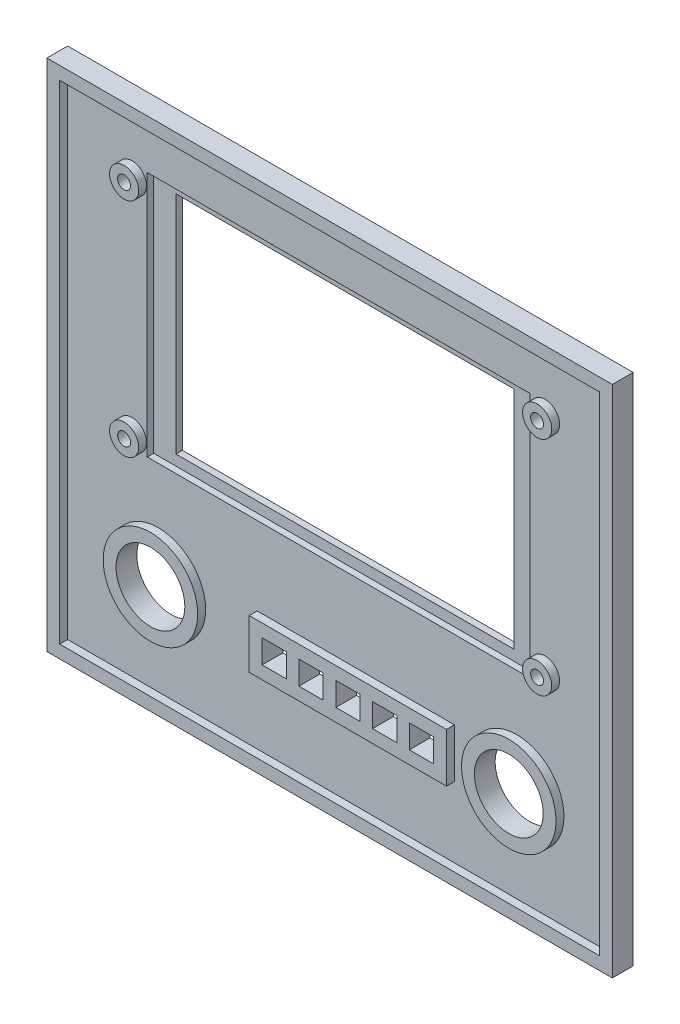
SolidWorks part; units mm, degrees
ref_plane "Front Plane" through (0, 0, 0) normal (0, 0, 1) x (1, 0, 0)
ref_plane "Top Plane" through (0, 0, 0) normal (0, 1, 0) x (1, 0, 0)
ref_plane "Right Plane" through (0, 0, 0) normal (1, 0, 0) x (0, 0, -1)
sketch "Sketch1" plane through (0, 0, 0) normal (0, 0, 1) x (1, 0, 0)
  line L0 (-7.852, -52.97) -> (-7.852, -58.77)
  line L1 (-41.76, -27.84) -> (41.76, -27.84)
  line L2 (-41.76, -27.84) -> (-41.76, 27.84)
  line L3 (-41.76, 27.84) -> (41.76, 27.84)
  line L4 (41.76, -27.84) -> (41.76, 27.84)
  line L5 (-41.76, -27.84) -> (41.76, 27.84) construction
  line L6 (-41.76, 27.84) -> (41.76, -27.84) construction
  line L7 (-70.1155, 44.4994) -> (69.5845, 44.4994)
  line L8 (-70.1155, 44.4994) -> (-70.1155, -82.5006)
  line L9 (-70.1155, -82.5006) -> (69.5845, -82.5006)
  line L10 (69.5845, 44.4994) -> (69.5845, -82.5006)
  line L11 (-16.9457, -52.97) -> (-10.9457, -52.97)
  line L12 (-16.9457, -52.97) -> (-16.9457, -58.77)
  line L13 (-16.9457, -58.77) -> (-10.9457, -58.77)
  line L14 (-10.9457, -52.97) -> (-10.9457, -58.77)
  line L15 (44.0042, -55.87) -> (-44.5351, -55.87) construction
  line L16 (-7.852, -52.97) -> (-1.852, -52.97)
  line L17 (-1.852, -52.97) -> (-1.852, -58.77)
  line L18 (-7.852, -58.77) -> (-1.852, -58.77)
  line L19 (1.2671, -52.97) -> (1.2671, -58.77)
  line L20 (1.2671, -52.97) -> (7.2671, -52.97)
  line L21 (7.2671, -52.97) -> (7.2671, -58.77)
  line L22 (1.2671, -58.77) -> (7.2671, -58.77)
  line L23 (10.3329, -52.97) -> (10.3329, -58.77)
  line L24 (10.3329, -52.97) -> (16.3329, -52.97)
  line L25 (16.3329, -52.97) -> (16.3329, -58.77)
  line L26 (10.3329, -58.77) -> (16.3329, -58.77)
  line L27 (-1.852, -55.87) -> (1.2671, -55.87) construction
  line L29 (-1.852, -55.87) -> (1.2671, -55.87) construction
  line L30 (-70.1155, -19.0006) -> (-58.5356, -19.0006) construction
  line L31 (58.0047, -19.0006) -> (69.5845, -19.0006) construction
  line L32 (-0.2655, -82.5006) -> (-0.2655, -69.8704) construction
  line L33 (-0.2655, 44.4994) -> (-0.2655, 31.8693) construction
  line L34 (-58.5356, 31.8693) -> (-58.5356, -69.8704)
  line L35 (58.0047, 31.8693) -> (-58.5356, 31.8693)
  line L36 (58.0047, -69.8704) -> (58.0047, 31.8693)
  line L37 (-58.5356, -69.8704) -> (58.0047, -69.8704)
  line L38 (-58.5356, 31.8693) -> (-58.5356, -69.8704) construction
  line L41 (-58.5356, -69.8704) -> (58.0047, -69.8704) construction
  line L49 (19.4266, -52.97) -> (19.4266, -58.77)
  line L50 (19.4266, -58.77) -> (25.4266, -58.77)
  line L51 (19.4266, -52.97) -> (25.4266, -52.97)
  line L52 (25.4266, -52.97) -> (25.4266, -58.77)
  line L53 (58.0047, -19.0006) -> (58.0047, 44.4994) construction
  line L54 (-58.5356, 31.8693) -> (69.5845, 31.8693) construction
  line L91 (58.0047, -69.8704) -> (58.0047, 44.4994) construction
  circle A0 centre (44.0042, -55.87) radius 8.5
  circle A1 centre (-44.5351, -55.87) radius 8.5
  point P0 (0, 0)
  point P16 (-16.9457, -55.87)
  dimension "D12" = 17
  dimension "D13" = 17
  dimension "D1" = 55.68
  dimension "D2" = 83.52
  dimension "D3" = 139.7
  dimension "D4" = 127
  dimension "D5" = 0
  dimension "D6" = 14.0005
  dimension "D7" = 14.0005
  dimension "D8" = 14.0005
  dimension "D9" = 14.0005
  dimension "D10" = 32.578
  dimension "D11" = 3.0937
  dimension "D14" = 6
  dimension "D15" = 5.8
  dimension "D17" = 3.0658
  dimension "D16" = 3.1191
  dimension "D18" = 3.0937
extrude "Boss-Extrude1" add sketch "Sketch1" along normal blind 5.1375 contours L9 L8 | A1 A0 L11 L14 L13 L12 L4 L1 L2 L3 L18 L0 L16 L17 L22 L19 L20 L21 L26 L23 L24 L25 | L9 L10 L7 L8 | L9 L8 region at (-0.2655, 42.6114, 0) region at (-0.5724, -28.913, 0)
sketch "Sketch2" plane through (0, 0, 5.1375) normal (0, 0, 1) x (1, 0, 0)
  line L0 (41.76, -27.84) -> (41.76, 27.84) construction
  line L1 (-41.76, -27.84) -> (41.76, -27.84) construction
  line L2 (-41.76, -27.84) -> (-41.76, 27.84) construction
  line L3 (-41.76, 27.84) -> (41.76, 27.84) construction
  line L4 (41.76, -27.84) -> (41.76, 27.84)
  line L5 (-41.76, -27.84) -> (41.76, -27.84)
  line L6 (-41.76, -27.84) -> (-41.76, 27.84)
  line L7 (-41.76, 27.84) -> (41.76, 27.84)
  line L9 (47.285, 30.44) -> (-47.285, 30.44)
  line L10 (47.285, 30.44) -> (47.285, -30.44)
  line L11 (47.285, -30.44) -> (-47.285, -30.44)
  line L12 (-47.285, 30.44) -> (-47.285, -30.44)
  line L13 (47.285, 30.44) -> (-47.285, -30.44) construction
  line L14 (47.285, -30.44) -> (-47.285, 30.44) construction
  point P3 (0, 0)
  dimension "D1" = 94.57
  dimension "D2" = 60.88
extrude "Cut-Extrude1" cut sketch "Sketch2" against normal blind 3.55
sketch "Sketch3" plane through (0, 0, 5.1375) normal (0, 0, 1) x (1, 0, 0)
  circle A0 centre (51.005, -27.4503) radius 1.6 construction
  circle A1 centre (-51.035, 27.4497) radius 1.6 construction
  circle A2 centre (51.005, 27.4497) radius 1.6 construction
  circle A3 centre (51.005, -27.4503) radius 1.6
  circle A4 centre (-51.035, 27.4497) radius 1.6
  circle A5 centre (51.005, 27.4497) radius 1.6
  circle A6 centre (-51.035, -27.4499) radius 1.6002 construction
  circle A7 centre (-51.035, -27.4499) radius 1.6002
extrude "Cut-Extrude2" cut sketch "Sketch3" against normal blind 10
sketch "Sketch4" plane through (0, 0, 5.1375) normal (0, 0, 1) x (1, 0, 0)
  line L1 (-20.1207, -49.795) -> (28.6016, -49.795)
  line L2 (-20.1207, -49.795) -> (-20.1207, -61.945)
  line L3 (-20.1207, -61.945) -> (28.6016, -61.945)
  line L4 (28.6016, -49.795) -> (28.6016, -61.945)
  line L8 (66.4095, -79.3256) -> (66.4095, 41.3244)
  line L9 (66.4095, 41.3244) -> (-66.9405, 41.3244)
  line L10 (-66.9405, 41.3244) -> (-66.9405, -79.3256)
  line L11 (-66.9405, -79.3256) -> (66.4095, -79.3256)
  line L12 (66.4095, -79.3256) -> (66.4095, 41.3244)
  line L13 (66.4095, 41.3244) -> (-66.9405, 41.3244)
  line L14 (-66.9405, 41.3244) -> (-66.9405, -79.3256)
  line L15 (-66.9405, -79.3256) -> (66.4095, -79.3256)
  circle A2 centre (44.0042, -55.87) radius 11.675
  circle A3 centre (44.0042, -55.87) radius 11.675
  circle A103 centre (-44.5351, -55.87) radius 11.675
  circle A104 centre (-44.5351, -55.87) radius 11.675
  arc A106 (-47.4348, -27.4499) -> (-47.4348, -27.4499) centre (-51.035, -27.4499) ccw
  circle A107 centre (-51.035, -27.4499) radius 3.6002
  arc A109 (-47.435, 27.4497) -> (-47.435, 27.4497) centre (-51.035, 27.4497) ccw
  circle A110 centre (-51.035, 27.4497) radius 3.6
  arc A116 (54.605, 27.4497) -> (54.605, 27.4497) centre (51.005, 27.4497) ccw
  circle A117 centre (51.005, 27.4497) radius 3.6
  arc A119 (54.605, -27.4503) -> (54.605, -27.4503) centre (51.005, -27.4503) ccw
  circle A120 centre (51.005, -27.4503) radius 3.6
  point P19 (0, 0)
  point P20 (0, 0)
  point P26 (18.4701, -64.4312)
  line M31 (-47.285, -30.44) -> (-47.285, 30.44)
  line M32 (-47.285, 30.44) -> (47.285, 30.44)
  line M33 (47.285, 30.44) -> (47.285, -30.44)
  line M34 (47.285, -30.44) -> (-47.285, -30.44)
  dimension "D7" = 3.175
  dimension "D8" = 3.175
  dimension "D9" = 3.175
  dimension "D10" = 3.175
  dimension "D1" = 3.175
  dimension "D2" = 3.175
  dimension "D3" = 2
  dimension "D4" = 2
  dimension "D5" = 2
  dimension "D6" = 2
  dimension "D11" = 3.175
extrude "Cut-Extrude3" cut sketch "Sketch4" against normal blind 1.9625 contours L14 L15 L12 L13 A120 A117 A110 A107 A104 A3 L1 L4 L3 L2 M34 M31 M32 M33 region at (-0.2655, -77.5273, 5.1375)
sketch "Text" plane through (0, 0, 0) normal (0, 0, -1) x (-1, 0, 0)
  line L0 (-69.5845, 32.4994) -> (70.1155, 32.4994) construction
  line L1 (-69.5845, 44.4994) -> (-69.5845, -82.5006) construction
  line L2 (70.1155, 44.4994) -> (70.1155, -82.5006) construction
  line L3 (70.1155, 44.4994) -> (-69.5845, 44.4994) construction
  line L4 (-31.3017, 35.4938) -> (-30.923, 37.63)
  line L5 (41.76, 27.84) -> (-41.76, 27.84) construction
  line L6 (-30.8297, 38.255) -> (-30.6282, 39.3128)
  line L7 (-31.3428, 40.4994) -> (-31.7345, 40.5218)
  line L8 (-31.6916, 40.7382) -> (-30.9286, 40.7382)
  line L9 (-30.9286, 40.7382) -> (-29.9976, 40.755)
  line L10 (-29.9976, 40.755) -> (-29.479, 40.7326)
  line L11 (-29.479, 40.7326) -> (-25.0834, 40.8576)
  line L12 (-25.9939, 40.6188) -> (-26.1581, 40.589)
  line L13 (-26.1581, 40.589) -> (-26.3577, 40.6039)
  line L14 (-26.3577, 40.6039) -> (-26.7905, 40.5293)
  line L15 (-26.7905, 40.5293) -> (-27.2793, 40.5293)
  line L16 (-27.2793, 40.5293) -> (-27.6301, 40.5143)
  line L17 (-27.6301, 40.5143) -> (-27.7551, 40.5293)
  line L18 (-27.7551, 40.5293) -> (-27.9939, 40.5143)
  line L19 (-27.9939, 40.5143) -> (-28.0946, 40.5143)
  line L20 (-28.0946, 40.5143) -> (-28.326, 40.4994)
  line L21 (-28.326, 40.4994) -> (-28.4827, 40.4994)
  line L22 (-28.4827, 40.4994) -> (-29.1095, 40.4826)
  line L23 (-29.6916, 39.9901) -> (-29.8428, 39.1673)
  line L24 (-29.8428, 39.1673) -> (-29.9752, 38.4024)
  line L25 (-29.9752, 38.4024) -> (-29.9939, 38.214)
  line L26 (-25.7644, 38.3128) -> (-25.5256, 38.3501)
  line L27 (-26.2345, 35.4975) -> (-26.242, 35.5293)
  line L28 (-29.2569, 36.7196) -> (-29.6935, 36.7028)
  line L29 (-29.6935, 36.7028) -> (-29.8129, 36.6934)
  line L30 (-30.5722, 35.1207) -> (-30.8931, 33.2438)
  line L31 (-29.7625, 32.6132) -> (-28.7905, 32.6599)
  line L32 (-28.7905, 32.6599) -> (-28.5536, 32.6729)
  line L33 (-28.5536, 32.6729) -> (-28.3931, 32.6654)
  line L34 (-25.1674, 34.5293) -> (-25.0592, 34.5293)
  line L35 (-27.354, 32.4994) -> (-28.2756, 32.449)
  line L36 (-28.2756, 32.449) -> (-28.5442, 32.449)
  line L37 (-28.5442, 32.449) -> (-29.3334, 32.38)
  line L38 (-29.3334, 32.38) -> (-29.9043, 32.4136)
  line L39 (-29.9043, 32.4136) -> (-30.5125, 32.3968)
  line L40 (-30.5125, 32.3968) -> (-31.8894, 32.4136)
  line L41 (-31.8894, 32.4136) -> (-32.1972, 32.38)
  line L42 (-32.1972, 32.38) -> (-32.7364, 32.3912)
  line L43 (-32.7364, 32.3912) -> (-33.2812, 32.3856)
  line L44 (-33.2812, 32.3856) -> (-33.2868, 32.5535)
  line L45 (-33.2868, 32.5535) -> (-32.6842, 32.5759)
  line L46 (-32.6842, 32.5759) -> (-32.2812, 32.6188)
  line L47 (-22.0984, 37.283) -> (-22.5405, 37.283)
  line L48 (-22.5405, 37.283) -> (-22.6991, 37.2886)
  line L49 (-22.6991, 37.2886) -> (-23.0648, 37.2755)
  line L50 (-23.0648, 37.2755) -> (-23.1375, 37.2755)
  line L51 (-20.6431, 38.9472) -> (-20.6301, 38.8725)
  line L52 (-21.0573, 37.5087) -> (-20.9155, 37.5087)
  line L53 (-20.9155, 37.5087) -> (-20.6842, 37.5013)
  line L54 (-20.6842, 37.5013) -> (-20.0331, 37.5143)
  line L55 (-21.4864, 37.1729) -> (-22.5069, 34.5181)
  line L56 (-23.0387, 33.1095) -> (-22.9566, 33.0964)
  line L57 (-23.5573, 33.5274) -> (-23.298, 34.1412)
  line L58 (-23.298, 34.1412) -> (-22.3838, 36.4845)
  line L59 (-18.0853, 34.1785) -> (-18.0032, 34.171)
  line L60 (-15.1618, 40.6188) -> (-15.1375, 40.7382)
  line L61 (-13.6898, 40.8576) -> (-13.7196, 40.7382)
  line L62 (-13.7196, 40.7382) -> (-13.8838, 40.3203)
  line L63 (-13.8838, 40.3203) -> (-14.242, 39.2793)
  line L64 (-17.186, 32.8259) -> (-16.7383, 33.9528)
  line L65 (-16.6692, 34.1169) -> (-14.9025, 39.2046)
  line L66 (-14.9025, 39.2046) -> (-14.6469, 39.936)
  line L67 (-11.4155, 35.2457) -> (-11.2868, 35.2513)
  line L68 (-11.2868, 35.2513) -> (-11.0946, 35.2513)
  line L69 (-10.7551, 35.2699) -> (-10.5648, 35.2643)
  line L70 (-10.5648, 35.2643) -> (-10.2607, 35.2774)
  line L71 (-10.2607, 35.2774) -> (-9.7308, 35.2643)
  line L72 (-9.4286, 34.6487) -> (-9.5387, 34.6673)
  line L73 (-8.3092, 32.9229) -> (-8.2122, 33.0069)
  line L74 (-8.2122, 33.0069) -> (-6.729, 34.4919)
  line L75 (-3.0125, 38.089) -> (-1.6357, 39.4285)
  line L76 (0.0005, 40.7251) -> (0.0061, 40.6561)
  line L77 (-0.0946, 39.186) -> (-0.1823, 38.061)
  line L78 (-0.2215, 37.3968) -> (-0.464, 34.464)
  line L79 (-0.464, 34.464) -> (-0.4584, 34.3259)
  line L80 (-0.4584, 34.3259) -> (-0.4715, 33.9994)
  line L81 (-0.4715, 33.9994) -> (-0.4715, 33.9061)
  line L82 (-0.4995, 33.7998) -> (-0.5125, 33.2625)
  line L83 (-0.5125, 33.2625) -> (-0.5051, 33.1804)
  line L84 (-0.5051, 33.1804) -> (-0.5256, 32.9304)
  line L85 (0.6181, 32.6188) -> (0.6237, 32.5349)
  line L86 (0.314, 32.436) -> (-0.4622, 32.4994)
  line L87 (-0.4622, 32.4994) -> (-1.0256, 32.4863)
  line L88 (-1.9211, 32.4192) -> (-2.0741, 32.4005)
  line L89 (-2.0741, 32.4005) -> (-2.2569, 32.4061)
  line L90 (-2.8129, 32.4024) -> (-2.7998, 32.5572)
  line L91 (-1.5984, 32.783) -> (-1.5666, 32.783)
  line L92 (-3.8782, 35.5479) -> (-5.1674, 35.4994)
  line L93 (-7.0107, 33.8819) -> (-7.4734, 33.3763)
  line L94 (-6.7122, 32.38) -> (-7.9062, 32.4994)
  line L95 (-7.9062, 32.4994) -> (-8.798, 32.4397)
  line L96 (-9.0965, 32.4136) -> (-9.1599, 32.4136)
  line L97 (-9.3857, 32.3893) -> (-9.6972, 32.38)
  line L98 (-9.8838, 32.5498) -> (-9.8054, 32.5722)
  line L99 (-9.8054, 32.5722) -> (-9.0872, 32.6188)
  line L100 (-9.0872, 32.6188) -> (-8.6431, 32.6953)
  line L101 (-3.4566, 35.7289) -> (-3.3036, 35.7289)
  line L102 (-3.3036, 35.7289) -> (-2.5163, 35.7606)
  line L103 (-2.5163, 35.7606) -> (-1.4864, 35.8203)
  line L104 (-1.145, 36.4957) -> (-1.0256, 38.3576)
  line L105 (-1.0256, 38.3576) -> (-0.9304, 39.5554)
  line L106 (-1.6655, 38.9807) -> (-3.117, 37.6039)
  line L107 (-3.117, 37.6039) -> (-3.3689, 37.3651)
  line L108 (-4.4528, 35.7177) -> (-4.1319, 35.7233)
  line L109 (1.7188, 35.2457) -> (1.8475, 35.2513)
  line L110 (1.8475, 35.2513) -> (2.0397, 35.2513)
  line L111 (2.3793, 35.2699) -> (2.5696, 35.2643)
  line L112 (2.5696, 35.2643) -> (2.8737, 35.2774)
  line L113 (2.8737, 35.2774) -> (3.4035, 35.2643)
  line L114 (3.7058, 34.6487) -> (3.5957, 34.6673)
  line L115 (6.5043, 40.7382) -> (7.0434, 40.7438)
  line L116 (7.0434, 40.7438) -> (7.2878, 40.7251)
  line L117 (7.2878, 40.7251) -> (7.8028, 40.7382)
  line L118 (7.8028, 40.7382) -> (8.48, 40.7326)
  line L119 (8.48, 40.7326) -> (8.939, 40.755)
  line L120 (8.939, 40.755) -> (9.5602, 40.7382)
  line L121 (9.5602, 40.7382) -> (10.0863, 40.7606)
  line L122 (12.6834, 40.977) -> (12.7841, 40.9584)
  line L123 (12.7841, 40.9584) -> (12.9222, 40.9584)
  line L124 (8.6666, 35.6654) -> (8.202, 33.3781)
  line L125 (9.5248, 32.5293) -> (9.4931, 32.38)
  line L126 (7.6311, 35.1207) -> (8.2095, 38.3744)
  line L127 (5.6386, 40.9826) -> (5.814, 40.9826)
  line L128 (5.814, 40.9826) -> (5.896, 40.977)
  line L129 (12.7692, 36.0815) -> (12.564, 36.1207)
  line L130 (12.8849, 33.1319) -> (12.8905, 33.0964)
  line L131 (16.9483, 36.2214) -> (15.6722, 33.3912)
  line L132 (15.5341, 32.977) -> (15.5789, 32.8576)
  line L133 (16.6479, 33.9322) -> (16.8625, 33.9024)
  line L134 (15.0994, 33.546) -> (16.0192, 35.5218)
  line L135 (12.4483, 33.6822) -> (13.5341, 35.7737)
  line L136 (13.5341, 35.7737) -> (13.9781, 36.6972)
  line L137 (19.8438, 36.2849) -> (19.4781, 35.3539)
  line L138 (21.6143, 34.5703) -> (20.9539, 33.1263)
  line L139 (20.9539, 33.1263) -> (20.9278, 33.0442)
  line L140 (22.0845, 33.9322) -> (22.355, 33.9266)
  line L141 (20.5285, 33.5516) -> (21.4446, 35.5479)
  line L142 (21.4446, 35.5479) -> (21.799, 36.3837)
  line L143 (18.4315, 34.3875) -> (18.5733, 34.7289)
  line L144 (18.5733, 34.7289) -> (19.3681, 36.8632)
  line L145 (25.5789, 34.171) -> (25.661, 34.171)
  line L146 (23.8998, 36.005) -> (24.3737, 36.7046)
  line L147 (25.9669, 35.6039) -> (25.4446, 35.2737)
  spline S0 degree 2 poles (-31.8017, 32.7513) (-31.7683, 32.9268) (-31.7439, 33.1039) knots 0 0 0 1 1 1
  spline S1 degree 3 poles (-31.7439, 33.1039) (-31.695, 33.3635) (-31.6191, 33.7372) (-31.5298, 34.2165) (-31.4692, 34.5303) (-31.417, 34.8139) (-31.3608, 35.1315) (-31.3243, 35.355) (-31.3017, 35.4938) knots 0 0 0 0 0.326061 0.470582 0.601853 0.720487 0.82649 1 1 1 1
  spline S2 degree 3 poles (-30.923, 37.63) (-30.9178, 37.6522) (-30.9104, 37.6933) (-30.8998, 37.7581) (-30.888, 37.8288) (-30.8783, 37.915) (-30.8548, 38.0582) (-30.8435, 38.1739) (-30.8297, 38.255) knots 0 0 0 0 0.108268 0.198044 0.311602 0.448536 0.609673 1 1 1 1
  spline S3 degree 3 poles (-30.6282, 39.3128) (-30.6087, 39.4131) (-30.5689, 39.6369) (-30.5536, 39.8638) (-30.5424, 39.9882) knots 0 0 0 0 0.449812 1 1 1 1
  spline S4 degree 2 poles (-30.5424, 39.9882) (-30.5378, 40.073) (-30.5368, 40.158) knots 0 0 0 1 1 1
  spline S5 degree 3 poles (-30.5368, 40.158) (-30.5347, 40.2033) (-30.5472, 40.2696) (-30.5933, 40.3435) (-30.6333, 40.3807) (-30.6782, 40.4055) (-30.7284, 40.4211) (-30.7925, 40.4377) (-30.8728, 40.4528) (-30.9683, 40.4644) (-31.1265, 40.4844) (-31.2533, 40.4915) (-31.3428, 40.4994) knots 0 0 0 0 0.139618 0.200722 0.265779 0.305214 0.357906 0.427115 0.508996 0.609481 0.723265 1 1 1 1
  spline S6 degree 2 poles (-31.7345, 40.5218) (-31.7293, 40.6332) (-31.6916, 40.7382) knots 0 0 0 1 1 1
  spline S7 degree 2 poles (-25.0834, 40.8576) (-24.9423, 40.8571) (-24.8017, 40.8446) knots 0 0 0 1 1 1
  spline S8 degree 2 poles (-24.8017, 40.8446) (-24.6861, 40.8392) (-24.5704, 40.839) knots 0 0 0 1 1 1
  spline S9 degree 3 poles (-24.5704, 40.839) (-24.5733, 40.8016) (-24.5776, 40.7386) (-24.5894, 40.6454) (-24.6029, 40.5542) (-24.6176, 40.4484) (-24.641, 40.2784) (-24.6635, 40.1445) (-24.6767, 40.0498) knots 0 0 0 0 0.141028 0.237774 0.353713 0.488533 0.639916 1 1 1 1
  spline S10 degree 3 poles (-24.6767, 40.0498) (-24.6943, 39.9342) (-24.731, 39.7242) (-24.7802, 39.5166) (-24.8092, 39.4248) knots 0 0 0 0 0.548362 1 1 1 1
  spline S11 degree 2 poles (-24.8092, 39.4248) (-24.94, 39.4348) (-25.048, 39.5087) knots 0 0 0 1 1 1
  spline S12 degree 3 poles (-25.048, 39.5087) (-25.0664, 39.6143) (-25.0945, 39.7805) (-25.1178, 39.9475) (-25.1226, 40.0087) knots 0 0 0 0 0.635671 1 1 1 1
  spline S13 degree 3 poles (-25.1226, 40.0087) (-25.1334, 40.0885) (-25.1291, 40.1933) (-25.1445, 40.309) (-25.1476, 40.3547) (-25.155, 40.3911) (-25.1767, 40.4567) (-25.1956, 40.5132) (-25.2103, 40.5554) knots 0 0 0 0 0.432733 0.560661 0.627956 0.679171 0.759662 1 1 1 1
  spline S14 degree 2 poles (-25.2103, 40.5554) (-25.3851, 40.5895) (-25.5629, 40.6001) knots 0 0 0 1 1 1
  spline S15 degree 2 poles (-25.5629, 40.6001) (-25.6601, 40.6079) (-25.7569, 40.6188) knots 0 0 0 1 1 1
  spline S16 degree 2 poles (-25.7569, 40.6188) (-25.8755, 40.6038) (-25.9939, 40.6188) knots 0 0 0 1 1 1
  spline S17 degree 2 poles (-29.1095, 40.4826) (-29.2556, 40.4723) (-29.3987, 40.4416) knots 0 0 0 1 1 1
  spline S18 degree 2 poles (-29.3987, 40.4416) (-29.5068, 40.4052) (-29.6114, 40.3595) knots 0 0 0 1 1 1
  spline S19 degree 2 poles (-29.6114, 40.3595) (-29.641, 40.1725) (-29.6916, 39.9901) knots 0 0 0 1 1 1
  spline S20 degree 3 poles (-29.9939, 38.214) (-30.0147, 38.0935) (-30.053, 37.9211) (-30.0891, 37.6988) (-30.1173, 37.5545) (-30.1365, 37.4235) (-30.1606, 37.2777) (-30.1747, 37.1749) (-30.1823, 37.1113) knots 0 0 0 0 0.327698 0.473272 0.603778 0.721938 0.828309 1 1 1 1
  spline S21 degree 2 poles (-30.1823, 37.1113) (-30.1886, 37.014) (-30.201, 36.9173) knots 0 0 0 1 1 1
  spline S22 degree 3 poles (-30.201, 36.9173) (-30.1252, 36.9227) (-29.9945, 36.9269) (-29.7968, 36.9375) (-29.5965, 36.9413) (-29.3614, 36.9492) (-28.979, 36.9638) (-28.6748, 36.9672) (-28.4603, 36.9751) knots 0 0 0 0 0.130845 0.225206 0.340938 0.475975 0.630317 1 1 1 1
  spline S23 degree 3 poles (-28.4603, 36.9751) (-28.2041, 36.9831) (-27.8458, 36.9908) (-27.4018, 37.0041) (-27.1456, 37.0136) (-26.9392, 37.0215) (-26.7662, 37.0266) (-26.6617, 37.0329) (-26.6095, 37.0367) knots 0 0 0 0 0.415223 0.580524 0.719646 0.83054 0.915221 1 1 1 1
  spline S24 degree 3 poles (-26.6095, 37.0367) (-26.5353, 37.0608) (-26.4289, 37.1045) (-26.3083, 37.1908) (-26.243, 37.2538) (-26.1956, 37.3229) (-26.1545, 37.3974) (-26.103, 37.493) (-26.0477, 37.6129) (-25.9875, 37.7562) (-25.8874, 37.9901) (-25.8173, 38.18) (-25.7644, 38.3128) knots 0 0 0 0 0.147484 0.213739 0.278288 0.316926 0.370926 0.438461 0.521183 0.619225 0.730946 1 1 1 1
  spline S25 degree 3 poles (-25.5256, 38.3501) (-25.5377, 38.2739) (-25.5517, 38.1489) (-25.5811, 37.9702) (-25.606, 37.8063) (-25.6395, 37.6234) (-25.6843, 37.3385) (-25.7267, 37.1158) (-25.7532, 36.9602) knots 0 0 0 0 0.164466 0.267686 0.38571 0.517451 0.66378 1 1 1 1
  spline S26 degree 2 poles (-25.7532, 36.9602) (-25.79, 36.7826) (-25.8073, 36.602) knots 0 0 0 1 1 1
  spline S27 degree 3 poles (-25.8073, 36.602) (-25.8184, 36.531) (-25.8476, 36.3531) (-25.8836, 36.1763) (-25.9062, 36.0703) knots 0 0 0 0 0.398632 1 1 1 1
  spline S28 degree 2 poles (-25.9062, 36.0703) (-25.9268, 35.9568) (-25.9435, 35.8427) knots 0 0 0 1 1 1
  spline S29 degree 3 poles (-25.9435, 35.8427) (-25.9554, 35.7728) (-25.9625, 35.6513) (-25.9923, 35.5335) (-26.0032, 35.4845) knots 0 0 0 0 0.585156 1 1 1 1
  spline S30 degree 2 poles (-26.0032, 35.4845) (-26.1186, 35.4964) (-26.2345, 35.4975) knots 0 0 0 1 1 1
  spline S31 degree 2 poles (-26.242, 35.5293) (-26.2357, 35.5913) (-26.2234, 35.6524) knots 0 0 0 1 1 1
  spline S32 degree 3 poles (-26.2234, 35.6524) (-26.2118, 35.7109) (-26.1914, 35.8604) (-26.193, 36.0113) (-26.1916, 36.102) knots 0 0 0 0 0.396387 1 1 1 1
  spline S33 degree 3 poles (-26.1916, 36.102) (-26.1902, 36.22) (-26.2003, 36.3825) (-26.2579, 36.5703) (-26.3188, 36.6666) (-26.4146, 36.7311) (-26.608, 36.791) (-26.7769, 36.7944) (-26.8987, 36.7979) knots 0 0 0 0 0.298411 0.406061 0.493081 0.579704 0.69083 1 1 1 1
  spline S34 degree 3 poles (-26.8987, 36.7979) (-27.0587, 36.8002) (-27.4071, 36.786) (-27.7554, 36.7697) (-27.9435, 36.7531) knots 0 0 0 0 0.45857 1 1 1 1
  spline S35 degree 3 poles (-27.9435, 36.7531) (-28.1301, 36.7544) (-28.5679, 36.7411) (-29.0058, 36.7318) (-29.2569, 36.7196) knots 0 0 0 0 0.426049 1 1 1 1
  spline S36 degree 2 poles (-29.8129, 36.6934) (-29.9475, 36.6959) (-30.0816, 36.6841) knots 0 0 0 1 1 1
  spline S37 degree 2 poles (-30.0816, 36.6841) (-30.1599, 36.6821) (-30.2383, 36.6785) knots 0 0 0 1 1 1
  spline S38 degree 3 poles (-30.2383, 36.6785) (-30.2667, 36.5322) (-30.313, 36.2906) (-30.3679, 36.0509) (-30.3894, 35.9565) knots 0 0 0 0 0.606091 1 1 1 1
  spline S39 degree 3 poles (-30.3894, 35.9565) (-30.4299, 35.7999) (-30.4948, 35.5221) (-30.553, 35.2428) (-30.5722, 35.1207) knots 0 0 0 0 0.566857 1 1 1 1
  spline S40 degree 2 poles (-30.8931, 33.2438) (-30.9085, 33.1333) (-30.9118, 33.0218) knots 0 0 0 1 1 1
  spline S41 degree 2 poles (-30.9118, 33.0218) (-30.9062, 32.9277) (-30.8689, 32.8408) knots 0 0 0 1 1 1
  spline S42 degree 3 poles (-30.8689, 32.8408) (-30.7996, 32.7742) (-30.6993, 32.6859) (-30.5441, 32.6536) (-30.3942, 32.6312) (-30.2661, 32.6299) (-30.173, 32.6263) knots 0 0 0 0 0.396116 0.492812 0.627983 1 1 1 1
  spline S43 degree 3 poles (-30.173, 32.6263) (-30.1338, 32.6271) (-30.0318, 32.6228) (-29.9298, 32.6224) (-29.867, 32.6188) knots 0 0 0 0 0.384087 1 1 1 1
  spline S44 degree 2 poles (-29.867, 32.6188) (-29.8148, 32.6149) (-29.7625, 32.6132) knots 0 0 0 1 1 1
  spline S45 degree 3 poles (-28.3931, 32.6654) (-28.2654, 32.6659) (-27.9935, 32.6826) (-27.7236, 32.7192) (-27.5816, 32.7457) knots 0 0 0 0 0.46924 1 1 1 1
  spline S46 degree 2 poles (-27.5816, 32.7457) (-27.4357, 32.7706) (-27.2887, 32.7867) knots 0 0 0 1 1 1
  spline S47 degree 3 poles (-27.2887, 32.7867) (-27.035, 32.8233) (-26.5334, 32.9539) (-26.0932, 33.2279) (-25.895, 33.3893) knots 0 0 0 0 0.500822 1 1 1 1
  spline S48 degree 3 poles (-25.895, 33.3893) (-25.7332, 33.5226) (-25.4404, 33.8782) (-25.2494, 34.2964) (-25.1674, 34.5293) knots 0 0 0 0 0.457872 1 1 1 1
  spline S49 degree 2 poles (-25.0592, 34.5293) (-24.9934, 34.5279) (-24.9286, 34.5162) knots 0 0 0 1 1 1
  spline S50 degree 3 poles (-24.9286, 34.5162) (-24.944, 34.4349) (-24.9766, 34.2921) (-25.0266, 34.0732) (-25.0815, 33.8445) (-25.1461, 33.5732) (-25.2557, 33.1261) (-25.3436, 32.7698) (-25.4062, 32.5181) knots 0 0 0 0 0.120763 0.213941 0.327814 0.464149 0.621184 1 1 1 1
  spline S51 degree 3 poles (-25.4062, 32.5181) (-25.5306, 32.5151) (-25.7265, 32.5118) (-26.0001, 32.506) (-26.2339, 32.5059) (-26.487, 32.4998) (-26.8627, 32.5031) (-27.1537, 32.4968) (-27.354, 32.4994) knots 0 0 0 0 0.191595 0.301756 0.421483 0.551755 0.691591 1 1 1 1
  spline S52 degree 3 poles (-32.2812, 32.6188) (-32.2132, 32.6359) (-32.0532, 32.6797) (-31.8932, 32.7233) (-31.8017, 32.7513) knots 0 0 0 0 0.423015 1 1 1 1
  spline S53 degree 2 poles (-23.1375, 37.2755) (-23.112, 37.4068) (-23.0312, 37.5143) knots 0 0 0 1 1 1
  spline S54 degree 3 poles (-23.0312, 37.5143) (-22.8948, 37.5228) (-22.7023, 37.5424) (-22.4606, 37.5605) (-22.3149, 37.5799) (-22.1913, 37.5904) (-22.0731, 37.6094) (-21.9956, 37.6213) (-21.9528, 37.6337) knots 0 0 0 0 0.377565 0.534527 0.669438 0.783477 0.877274 1 1 1 1
  spline S55 degree 2 poles (-21.9528, 37.6337) (-21.8558, 37.8307) (-21.7476, 38.0218) knots 0 0 0 1 1 1
  spline S56 degree 3 poles (-21.7476, 38.0218) (-21.6821, 38.1397) (-21.5457, 38.3945) (-21.4301, 38.6594) (-21.367, 38.7998) knots 0 0 0 0 0.467164 1 1 1 1
  spline S57 degree 2 poles (-21.367, 38.7998) (-21.3081, 38.9373) (-21.2327, 39.0666) knots 0 0 0 1 1 1
  spline S58 degree 3 poles (-21.2327, 39.0666) (-21.1907, 39.1059) (-21.0919, 39.1648) (-20.9791, 39.1871) (-20.923, 39.186) knots 0 0 0 0 0.50595 1 1 1 1
  spline S59 degree 3 poles (-20.923, 39.186) (-20.8684, 39.1865) (-20.7503, 39.1234) (-20.6805, 39.0116) (-20.6431, 38.9472) knots 0 0 0 0 0.411802 1 1 1 1
  spline S60 degree 3 poles (-20.6301, 38.8725) (-20.6363, 38.8383) (-20.6643, 38.777) (-20.713, 38.678) (-20.7724, 38.5624) (-20.8515, 38.4213) (-20.9888, 38.1786) (-21.1022, 37.9845) (-21.1842, 37.8464) knots 0 0 0 0 0.088649 0.172237 0.283692 0.422404 0.587653 1 1 1 1
  spline S61 degree 2 poles (-21.1842, 37.8464) (-21.2432, 37.7405) (-21.2887, 37.6281) knots 0 0 0 1 1 1
  spline S62 degree 3 poles (-21.2887, 37.6281) (-21.238, 37.5949) (-21.1615, 37.5547) (-21.0843, 37.5129) (-21.0573, 37.5087) knots 0 0 0 0 0.691086 1 1 1 1
  spline S63 degree 3 poles (-20.0331, 37.5143) (-20.033, 37.4689) (-20.0521, 37.3752) (-20.1162, 37.3043) (-20.1525, 37.2755) knots 0 0 0 0 0.494327 1 1 1 1
  spline S64 degree 3 poles (-20.1525, 37.2755) (-20.2522, 37.2627) (-20.48, 37.2534) (-20.7077, 37.2466) (-20.8353, 37.2475) knots 0 0 0 0 0.44047 1 1 1 1
  spline S65 degree 3 poles (-20.8353, 37.2475) (-20.8925, 37.2487) (-20.9815, 37.2466) (-21.0704, 37.2437) (-21.1021, 37.2419) knots 0 0 0 0 0.643205 1 1 1 1
  spline S66 degree 3 poles (-21.1021, 37.2419) (-21.1904, 37.237) (-21.3181, 37.2135) (-21.4479, 37.1925) (-21.4864, 37.1729) knots 0 0 0 0 0.673132 1 1 1 1
  spline S67 degree 3 poles (-22.5069, 34.5181) (-22.5383, 34.4473) (-22.5898, 34.3315) (-22.6604, 34.1626) (-22.7286, 34.007) (-22.8044, 33.8318) (-22.9195, 33.5574) (-23.0118, 33.3433) (-23.076, 33.1934) knots 0 0 0 0 0.161092 0.263726 0.380803 0.514702 0.660836 1 1 1 1
  spline S68 degree 2 poles (-23.076, 33.1934) (-23.0712, 33.1456) (-23.0387, 33.1095) knots 0 0 0 1 1 1
  spline S69 degree 3 poles (-22.9566, 33.0964) (-22.8888, 33.0983) (-22.7338, 33.157) (-22.607, 33.2615) (-22.5349, 33.324) knots 0 0 0 0 0.410692 1 1 1 1
  spline S70 degree 3 poles (-22.5349, 33.324) (-22.3542, 33.4841) (-21.9953, 33.8263) (-21.6803, 34.2093) (-21.5256, 34.4099) knots 0 0 0 0 0.487962 1 1 1 1
  spline S71 degree 2 poles (-21.5256, 34.4099) (-21.4266, 34.3552) (-21.3465, 34.2755) knots 0 0 0 1 1 1
  spline S72 degree 3 poles (-21.3465, 34.2755) (-21.4397, 34.1567) (-21.5715, 33.9844) (-21.747, 33.7718) (-21.8585, 33.6347) (-21.9601, 33.5154) (-22.0481, 33.4108) (-22.1276, 33.3247) (-22.2175, 33.2287) (-22.3321, 33.1202) (-22.4797, 32.9933) (-22.6446, 32.8646) (-22.8177, 32.7396) (-22.9779, 32.624) (-23.1322, 32.5273) (-23.2246, 32.4618) (-23.2793, 32.4378) knots 0 0 0 0 0.168489 0.241953 0.30751 0.365604 0.416774 0.459988 0.496303 0.563527 0.635842 0.713423 0.79682 0.874003 0.933654 1 1 1 1
  spline S73 degree 2 poles (-23.2793, 32.4378) (-23.4146, 32.3817) (-23.561, 32.38) knots 0 0 0 1 1 1
  spline S74 degree 3 poles (-23.561, 32.38) (-23.6338, 32.3787) (-23.8098, 32.4067) (-23.8559, 32.5756) (-23.854, 32.6431) knots 0 0 0 0 0.526102 1 1 1 1
  spline S75 degree 3 poles (-23.854, 32.6431) (-23.855, 32.6857) (-23.8385, 32.7558) (-23.8125, 32.8604) (-23.7771, 32.9622) (-23.7372, 33.0816) (-23.665, 33.2727) (-23.6006, 33.4216) (-23.5573, 33.5274) knots 0 0 0 0 0.135335 0.230085 0.345427 0.480311 0.633572 1 1 1 1
  spline S76 degree 3 poles (-22.3838, 36.4845) (-22.3277, 36.6257) (-22.2315, 36.8915) (-22.1385, 37.1585) (-22.0984, 37.283) knots 0 0 0 0 0.537368 1 1 1 1
  spline S77 degree 2 poles (-17.4808, 36.3763) (-17.5677, 36.4696) (-17.6319, 36.5796) knots 0 0 0 1 1 1
  spline S78 degree 3 poles (-17.6319, 36.5796) (-17.6507, 36.619) (-17.6789, 36.6943) (-17.7188, 36.814) (-17.7595, 36.9364) (-17.7973, 37.0594) (-17.8421, 37.1786) (-17.8697, 37.2551) (-17.895, 37.2923) knots 0 0 0 0 0.171759 0.316791 0.497498 0.680537 0.824068 1 1 1 1
  spline S79 degree 2 poles (-17.895, 37.2923) (-17.9541, 37.3827) (-18.0592, 37.3949) knots 0 0 0 1 1 1
  spline S80 degree 3 poles (-18.0592, 37.3949) (-18.1443, 37.396) (-18.3313, 37.3285) (-18.4779, 37.1966) (-18.5536, 37.1169) knots 0 0 0 0 0.430993 1 1 1 1
  spline S81 degree 3 poles (-18.5536, 37.1169) (-18.6418, 37.0232) (-18.7683, 36.8667) (-18.9242, 36.6346) (-19.0469, 36.4336) (-19.1698, 36.2112) (-19.2928, 35.9675) (-19.4175, 35.7041) (-19.5379, 35.425) (-19.6523, 35.143) (-19.7526, 34.8672) (-19.8398, 34.6045) (-19.9078, 34.3531) (-19.9662, 34.1155) (-20.0124, 33.8223) (-20.035, 33.6085) (-20.0331, 33.4696) knots 0 0 0 0 0.096601 0.15073 0.209825 0.273359 0.34143 0.414738 0.492108 0.569618 0.643175 0.712422 0.777327 0.838709 0.89597 1 1 1 1
  spline S82 degree 3 poles (-20.0331, 33.4696) (-20.0313, 33.3869) (-20.028, 33.2432) (-19.9761, 33.1088) (-19.9416, 33.061) knots 0 0 0 0 0.586985 1 1 1 1
  spline S83 degree 2 poles (-19.9416, 33.061) (-19.8604, 32.9713) (-19.7383, 32.977) knots 0 0 0 1 1 1
  spline S84 degree 3 poles (-19.7383, 32.977) (-19.6383, 32.9748) (-19.4234, 33.0363) (-19.2332, 33.151) (-19.1375, 33.227) knots 0 0 0 0 0.447291 1 1 1 1
  spline S85 degree 3 poles (-19.1375, 33.227) (-18.9783, 33.3464) (-18.6611, 33.639) (-18.3823, 33.968) (-18.242, 34.1524) knots 0 0 0 0 0.461802 1 1 1 1
  spline S86 degree 2 poles (-18.242, 34.1524) (-18.1653, 34.1761) (-18.0853, 34.1785) knots 0 0 0 1 1 1
  spline S87 degree 3 poles (-18.0032, 34.171) (-18.0104, 34.1436) (-18.0312, 34.0987) (-18.0663, 34.0327) (-18.1071, 33.9661) (-18.1563, 33.8878) (-18.2387, 33.7588) (-18.3104, 33.6607) (-18.3577, 33.589) knots 0 0 0 0 0.123894 0.21673 0.32818 0.466817 0.622837 1 1 1 1
  spline S88 degree 3 poles (-18.3577, 33.589) (-18.4987, 33.3895) (-18.7102, 33.1162) (-19.0149, 32.8099) (-19.2234, 32.6488) (-19.421, 32.529) (-19.663, 32.4213) (-19.8488, 32.38) (-19.9696, 32.38) knots 0 0 0 0 0.351493 0.495695 0.620031 0.729551 0.827266 1 1 1 1
  spline S89 degree 3 poles (-19.9696, 32.38) (-20.0581, 32.3791) (-20.2318, 32.4105) (-20.3715, 32.5187) (-20.4211, 32.5852) knots 0 0 0 0 0.518062 1 1 1 1
  spline S90 degree 3 poles (-20.4211, 32.5852) (-20.5007, 32.687) (-20.6092, 32.9677) (-20.6295, 33.2659) (-20.6301, 33.4341) knots 0 0 0 0 0.431038 1 1 1 1
  spline S91 degree 3 poles (-20.6301, 33.4341) (-20.631, 33.6208) (-20.5898, 33.9135) (-20.4947, 34.3178) (-20.3888, 34.6581) (-20.2558, 35.0106) (-20.0878, 35.3601) (-19.8937, 35.7043) (-19.6757, 36.0327) (-19.455, 36.3344) (-19.25, 36.5969) (-19.0706, 36.8154) (-18.9042, 36.9915) (-18.7382, 37.1373) (-18.5001, 37.3164) (-18.2978, 37.422) (-18.1599, 37.4901) knots 0 0 0 0 0.113117 0.179139 0.252321 0.329621 0.407913 0.487814 0.569704 0.647361 0.714967 0.772131 0.819191 0.862045 0.906351 1 1 1 1
  spline S92 degree 3 poles (-18.1599, 37.4901) (-18.0681, 37.5354) (-17.8871, 37.6065) (-17.6945, 37.6329) (-17.604, 37.6337) knots 0 0 0 0 0.53107 1 1 1 1
  spline S93 degree 3 poles (-17.604, 37.6337) (-17.5166, 37.6341) (-17.3843, 37.5972) (-17.2325, 37.4884) (-17.1295, 37.3753) (-17.0403, 37.2424) (-16.9509, 37.0428) (-16.9298, 36.8775) (-16.9286, 36.7681) knots 0 0 0 0 0.215662 0.330966 0.459948 0.593638 0.727131 1 1 1 1
  spline S94 degree 3 poles (-16.9286, 36.7681) (-16.9259, 36.7041) (-16.9396, 36.6129) (-16.983, 36.5026) (-17.0286, 36.438) (-17.0798, 36.3843) (-17.1592, 36.337) (-17.225, 36.319) (-17.27, 36.3203) knots 0 0 0 0 0.304198 0.436111 0.562239 0.679926 0.787988 1 1 1 1
  spline S95 degree 2 poles (-17.27, 36.3203) (-17.3804, 36.3286) (-17.4808, 36.3763) knots 0 0 0 1 1 1
  spline S96 degree 3 poles (-15.1375, 40.7382) (-14.9814, 40.7561) (-14.7605, 40.7861) (-14.4819, 40.813) (-14.3125, 40.8336) (-14.1685, 40.8449) (-14.0284, 40.8602) (-13.9355, 40.8642) (-13.8819, 40.8651) knots 0 0 0 0 0.373605 0.529638 0.664941 0.779212 0.872743 1 1 1 1
  spline S97 degree 2 poles (-13.8819, 40.8651) (-13.7858, 40.8639) (-13.6898, 40.8576) knots 0 0 0 1 1 1
  spline S98 degree 3 poles (-14.242, 39.2793) (-14.2774, 39.1789) (-14.3609, 38.9347) (-14.4349, 38.6874) (-14.479, 38.5423) knots 0 0 0 0 0.412294 1 1 1 1
  spline S99 degree 3 poles (-14.479, 38.5423) (-14.5701, 38.2488) (-14.7055, 37.8181) (-14.9097, 37.2663) (-15.0634, 36.8795) (-15.22, 36.498) (-15.4159, 35.964) (-15.5501, 35.5519) (-15.6375, 35.2718) knots 0 0 0 0 0.265691 0.390006 0.508485 0.625467 0.746383 1 1 1 1
  spline S100 degree 3 poles (-15.6375, 35.2718) (-15.5981, 35.32) (-15.515, 35.4359) (-15.4317, 35.5516) (-15.3875, 35.6188) knots 0 0 0 0 0.436177 1 1 1 1
  spline S101 degree 3 poles (-15.3875, 35.6188) (-15.246, 35.8123) (-15.0395, 36.0917) (-14.7576, 36.438) (-14.5637, 36.664) (-14.3799, 36.866) (-14.1566, 37.0894) (-13.9879, 37.2383) (-13.8745, 37.324) knots 0 0 0 0 0.314594 0.455513 0.585679 0.705203 0.813655 1 1 1 1
  spline S102 degree 3 poles (-13.8745, 37.324) (-13.7481, 37.4175) (-13.4927, 37.5738) (-13.1988, 37.6343) (-13.061, 37.6337) knots 0 0 0 0 0.534604 1 1 1 1
  spline S103 degree 3 poles (-13.061, 37.6337) (-12.9569, 37.6348) (-12.8007, 37.5996) (-12.6192, 37.4865) (-12.4978, 37.3671) (-12.3932, 37.2147) (-12.2902, 36.9427) (-12.274, 36.7122) (-12.2719, 36.5516) knots 0 0 0 0 0.207527 0.311313 0.423786 0.545439 0.677649 1 1 1 1
  spline S104 degree 3 poles (-12.2719, 36.5516) (-12.272, 36.4288) (-12.2843, 36.2402) (-12.3213, 35.9843) (-12.3605, 35.7795) (-12.4112, 35.5667) (-12.4729, 35.3464) (-12.5463, 35.1182) (-12.6559, 34.809) (-12.8067, 34.4364) (-13.0103, 34.0233) (-13.2269, 33.6519) (-13.4291, 33.3802) (-13.5905, 33.1847) (-13.7075, 33.0564) (-13.8161, 32.938) (-13.9231, 32.8351) (-14.0255, 32.7458) (-14.1226, 32.6683) (-14.2159, 32.6042) (-14.333, 32.539) (-14.4728, 32.4767) (-14.6803, 32.4048) (-14.8371, 32.3812) (-14.9379, 32.38) knots 0 0 0 0 0.069561 0.106928 0.146381 0.187654 0.230821 0.275944 0.323412 0.416639 0.503452 0.584173 0.65978 0.695054 0.727735 0.758143 0.786048 0.811766 0.835095 0.856397 0.875799 0.910962 0.942936 1 1 1 1
  spline S105 degree 3 poles (-14.9379, 32.38) (-15.0096, 32.3804) (-15.1414, 32.3885) (-15.261, 32.4445) (-15.3073, 32.4789) knots 0 0 0 0 0.556277 1 1 1 1
  spline S106 degree 3 poles (-15.3073, 32.4789) (-15.3603, 32.521) (-15.4539, 32.6053) (-15.4966, 32.7246) (-15.4957, 32.7793) knots 0 0 0 0 0.559488 1 1 1 1
  spline S107 degree 3 poles (-15.4957, 32.7793) (-15.49, 32.8412) (-15.3739, 32.9496) (-15.224, 32.9809) (-15.1319, 32.977) knots 0 0 0 0 0.387351 1 1 1 1
  spline S108 degree 3 poles (-15.1319, 32.977) (-15.064, 32.9779) (-14.972, 32.9643) (-14.8814, 32.899) (-14.8003, 32.8246) (-14.7406, 32.7535) (-14.6972, 32.7009) knots 0 0 0 0 0.387023 0.484167 0.619211 1 1 1 1
  spline S109 degree 2 poles (-14.6972, 32.7009) (-14.6216, 32.6322) (-14.5219, 32.6188) knots 0 0 0 1 1 1
  spline S110 degree 3 poles (-14.5219, 32.6188) (-14.4662, 32.6216) (-14.3423, 32.7064) (-14.2536, 32.8213) (-14.1954, 32.8931) knots 0 0 0 0 0.366711 1 1 1 1
  spline S111 degree 3 poles (-14.1954, 32.8931) (-14.1159, 32.9991) (-14.0069, 33.1814) (-13.8685, 33.4498) (-13.7548, 33.6942) (-13.6404, 33.9707) (-13.4741, 34.3973) (-13.3544, 34.735) (-13.2775, 34.9714) knots 0 0 0 0 0.174055 0.279112 0.397381 0.528708 0.67279 1 1 1 1
  spline S112 degree 3 poles (-13.2775, 34.9714) (-13.2164, 35.1612) (-13.1249, 35.4349) (-13.0304, 35.7929) (-12.9715, 36.0314) (-12.9262, 36.2517) (-12.8862, 36.5082) (-12.8671, 36.6921) (-12.8689, 36.8091) knots 0 0 0 0 0.316696 0.457778 0.587828 0.706734 0.814693 1 1 1 1
  spline S113 degree 3 poles (-12.8689, 36.8091) (-12.8676, 36.9053) (-12.8761, 37.0377) (-12.9165, 37.194) (-12.9603, 37.273) (-13.0162, 37.3269) (-13.0988, 37.3841) (-13.177, 37.3938) (-13.2271, 37.3949) knots 0 0 0 0 0.370177 0.507175 0.617532 0.712239 0.803783 1 1 1 1
  spline S114 degree 2 poles (-13.2271, 37.3949) (-13.336, 37.3913) (-13.4323, 37.339) knots 0 0 0 1 1 1
  spline S115 degree 3 poles (-13.4323, 37.339) (-13.5604, 37.2758) (-13.7494, 37.1511) (-13.9906, 36.9452) (-14.155, 36.788) (-14.2949, 36.6367) (-14.4193, 36.499) (-14.5535, 36.3333) (-14.7077, 36.1481) (-14.8731, 35.9362) (-15.1254, 35.608) (-15.3216, 35.3495) (-15.4547, 35.1673) knots 0 0 0 0 0.142952 0.226178 0.317944 0.370905 0.43276 0.504085 0.584756 0.674485 0.773679 1 1 1 1
  spline S116 degree 3 poles (-15.4547, 35.1673) (-15.4905, 35.1104) (-15.5522, 35.0168) (-15.6276, 34.8713) (-15.7021, 34.7341) (-15.7779, 34.573) (-15.8679, 34.3944) (-15.9591, 34.1919) (-16.0601, 33.9771) (-16.1571, 33.7586) (-16.2507, 33.5525) (-16.3344, 33.3631) (-16.4119, 33.1915) (-16.4784, 33.0357) (-16.5503, 32.8625) (-16.6019, 32.7424) (-16.6319, 32.6673) knots 0 0 0 0 0.07301 0.121302 0.177729 0.242291 0.314394 0.394677 0.48311 0.571878 0.654001 0.72859 0.796534 0.858183 0.912305 1 1 1 1
  spline S117 degree 3 poles (-16.6319, 32.6673) (-16.6551, 32.6138) (-16.6962, 32.5451) (-16.7538, 32.4655) (-16.8425, 32.3928) (-16.9418, 32.3818) (-17.0125, 32.38) knots 0 0 0 0 0.338471 0.467712 0.57088 1 1 1 1
  spline S118 degree 3 poles (-17.0125, 32.38) (-17.0765, 32.3861) (-17.2332, 32.382) (-17.2885, 32.52) (-17.2868, 32.5722) knots 0 0 0 0 0.575901 1 1 1 1
  spline S119 degree 3 poles (-17.2868, 32.5722) (-17.2828, 32.5974) (-17.2398, 32.6787) (-17.2191, 32.7681) (-17.186, 32.8259) knots 0 0 0 0 0.277191 1 1 1 1
  spline S120 degree 2 poles (-16.7383, 33.9528) (-16.7022, 34.0342) (-16.6692, 34.1169) knots 0 0 0 1 1 1
  spline S121 degree 3 poles (-14.6469, 39.936) (-14.619, 40.0123) (-14.5751, 40.1346) (-14.5472, 40.2621) (-14.5461, 40.311) knots 0 0 0 0 0.625427 1 1 1 1
  spline S122 degree 3 poles (-14.5461, 40.311) (-14.5426, 40.3517) (-14.5737, 40.4524) (-14.6787, 40.4769) (-14.7252, 40.4863) knots 0 0 0 0 0.447781 1 1 1 1
  spline S123 degree 2 poles (-14.7252, 40.4863) (-14.9501, 40.531) (-15.1618, 40.6188) knots 0 0 0 1 1 1
  spline S124 degree 3 poles (-11.6748, 34.6487) (-11.6469, 34.7315) (-11.5718, 34.8906) (-11.4962, 35.0493) (-11.464, 35.1319) knots 0 0 0 0 0.496329 1 1 1 1
  spline S125 degree 2 poles (-11.464, 35.1319) (-11.44, 35.1889) (-11.4155, 35.2457) knots 0 0 0 1 1 1
  spline S126 degree 3 poles (-11.0946, 35.2513) (-11.056, 35.2526) (-10.9428, 35.2588) (-10.8297, 35.2653) (-10.7551, 35.2699) knots 0 0 0 0 0.340543 1 1 1 1
  spline S127 degree 2 poles (-9.7308, 35.2643) (-9.6291, 35.2624) (-9.5275, 35.2587) knots 0 0 0 1 1 1
  spline S128 degree 3 poles (-9.5275, 35.2587) (-9.4703, 35.2622) (-9.3857, 35.2669) (-9.3011, 35.2705) (-9.2737, 35.2699) knots 0 0 0 0 0.676706 1 1 1 1
  spline S129 degree 2 poles (-9.2737, 35.2699) (-9.1718, 35.2691) (-9.0704, 35.2587) knots 0 0 0 1 1 1
  spline S130 degree 2 poles (-9.0704, 35.2587) (-8.9999, 35.2478) (-8.9286, 35.2457) knots 0 0 0 1 1 1
  spline S131 degree 3 poles (-8.9286, 35.2457) (-8.9659, 35.1296) (-9.0343, 34.9256) (-9.1224, 34.7291) (-9.1692, 34.6487) knots 0 0 0 0 0.567428 1 1 1 1
  spline S132 degree 2 poles (-9.1692, 34.6487) (-9.2989, 34.6487) (-9.4286, 34.6487) knots 0 0 0 1 1 1
  spline S133 degree 3 poles (-9.5387, 34.6673) (-9.6153, 34.6657) (-9.7308, 34.6569) (-9.8466, 34.6528) (-9.8857, 34.6487) knots 0 0 0 0 0.661083 1 1 1 1
  spline S134 degree 2 poles (-9.8857, 34.6487) (-10.029, 34.6763) (-10.1748, 34.6785) knots 0 0 0 1 1 1
  spline S135 degree 3 poles (-10.1748, 34.6785) (-10.3589, 34.6783) (-10.6801, 34.6756) (-11.001, 34.6603) (-11.1375, 34.6487) knots 0 0 0 0 0.573287 1 1 1 1
  spline S136 degree 3 poles (-11.1375, 34.6487) (-11.2128, 34.6487) (-11.3919, 34.6487) (-11.571, 34.6487) (-11.6748, 34.6487) knots 0 0 0 0 0.420139 1 1 1 1
  spline S137 degree 2 poles (-8.4995, 32.7718) (-8.4037, 32.8466) (-8.3092, 32.9229) knots 0 0 0 1 1 1
  spline S138 degree 3 poles (-6.729, 34.4919) (-6.6587, 34.5616) (-6.5666, 34.6561) (-6.4534, 34.7619) (-6.3806, 34.8232) (-6.2998, 34.8929) (-6.208, 34.9953) (-6.0974, 35.1153) (-5.9257, 35.2776) (-5.7953, 35.4053) (-5.714, 35.4901) knots 0 0 0 0 0.208434 0.277967 0.326279 0.408855 0.502458 0.615534 0.752647 1 1 1 1
  spline S139 degree 3 poles (-5.714, 35.4901) (-5.641, 35.5557) (-5.523, 35.662) (-5.4114, 35.7752) (-5.3707, 35.8203) knots 0 0 0 0 0.617873 1 1 1 1
  spline S140 degree 3 poles (-5.3707, 35.8203) (-5.2078, 35.9682) (-4.9577, 36.2025) (-4.6138, 36.5304) (-4.3271, 36.8028) (-4.0244, 37.0977) (-3.5822, 37.5261) (-3.2431, 37.8593) (-3.0125, 38.089) knots 0 0 0 0 0.201697 0.314205 0.43558 0.564193 0.701674 1 1 1 1
  spline S141 degree 2 poles (-1.6357, 39.4285) (-1.511, 39.568) (-1.3689, 39.6897) knots 0 0 0 1 1 1
  spline S142 degree 3 poles (-1.3689, 39.6897) (-1.2522, 39.8236) (-1.0472, 40.0562) (-0.8387, 40.2856) (-0.7476, 40.3819) knots 0 0 0 0 0.572681 1 1 1 1
  spline S143 degree 3 poles (-0.7476, 40.3819) (-0.7036, 40.4185) (-0.5883, 40.5348) (-0.4698, 40.6476) (-0.3969, 40.7251) knots 0 0 0 0 0.34962 1 1 1 1
  spline S144 degree 2 poles (-0.3969, 40.7251) (-0.3133, 40.737) (-0.229, 40.7382) knots 0 0 0 1 1 1
  spline S145 degree 2 poles (-0.229, 40.7382) (-0.114, 40.7355) (0.0005, 40.7251) knots 0 0 0 1 1 1
  spline S146 degree 3 poles (0.0061, 40.6561) (-0.0059, 40.5075) (-0.0306, 40.2599) (-0.038, 40.0112) (-0.0405, 39.9117) knots 0 0 0 0 0.599582 1 1 1 1
  spline S147 degree 3 poles (-0.0405, 39.9117) (-0.0577, 39.8091) (-0.0857, 39.5677) (-0.0927, 39.3247) (-0.0946, 39.186) knots 0 0 0 0 0.428327 1 1 1 1
  spline S148 degree 3 poles (-0.1823, 38.061) (-0.189, 37.9839) (-0.2053, 37.7627) (-0.2112, 37.5409) (-0.2215, 37.3968) knots 0 0 0 0 0.348613 1 1 1 1
  spline S149 degree 2 poles (-0.4715, 33.9061) (-0.4857, 33.853) (-0.4995, 33.7998) knots 0 0 0 1 1 1
  spline S150 degree 3 poles (-0.5256, 32.9304) (-0.506, 32.8893) (-0.4116, 32.8326) (-0.3084, 32.8046) (-0.2439, 32.7998) knots 0 0 0 0 0.402513 1 1 1 1
  spline S151 degree 3 poles (-0.2439, 32.7998) (-0.0741, 32.7821) (0.2172, 32.7383) (0.503, 32.665) (0.6181, 32.6188) knots 0 0 0 0 0.579632 1 1 1 1
  spline S152 degree 2 poles (0.6237, 32.5349) (0.6195, 32.4552) (0.5919, 32.38) knots 0 0 0 1 1 1
  spline S153 degree 3 poles (0.5919, 32.38) (0.531, 32.3932) (0.4388, 32.4141) (0.3458, 32.4314) (0.314, 32.436) knots 0 0 0 0 0.659298 1 1 1 1
  spline S154 degree 3 poles (-1.0256, 32.4863) (-1.1911, 32.4646) (-1.4893, 32.4358) (-1.7884, 32.4182) (-1.9211, 32.4192) knots 0 0 0 0 0.557254 1 1 1 1
  spline S155 degree 3 poles (-2.2569, 32.4061) (-2.3302, 32.398) (-2.4398, 32.3915) (-2.5491, 32.3809) (-2.5853, 32.38) knots 0 0 0 0 0.670696 1 1 1 1
  spline S156 degree 2 poles (-2.5853, 32.38) (-2.7, 32.3819) (-2.8129, 32.4024) knots 0 0 0 1 1 1
  spline S157 degree 2 poles (-2.7998, 32.5572) (-2.599, 32.6041) (-2.3931, 32.6188) knots 0 0 0 1 1 1
  spline S158 degree 2 poles (-2.3931, 32.6188) (-2.0415, 32.6442) (-1.7084, 32.7587) knots 0 0 0 1 1 1
  spline S159 degree 2 poles (-1.7084, 32.7587) (-1.655, 32.7787) (-1.5984, 32.783) knots 0 0 0 1 1 1
  spline S160 degree 2 poles (-1.5666, 32.783) (-1.5058, 32.8508) (-1.4808, 32.9378) knots 0 0 0 1 1 1
  spline S161 degree 3 poles (-1.4808, 32.9378) (-1.4726, 32.9731) (-1.458, 33.038) (-1.4445, 33.1412) (-1.4291, 33.2537) (-1.4127, 33.3893) (-1.3939, 33.5485) (-1.3735, 33.7313) (-1.3445, 33.9986) (-1.3115, 34.3244) (-1.275, 34.7689) (-1.2539, 35.0761) (-1.2532, 35.2643) knots 0 0 0 0 0.046459 0.085145 0.133421 0.192081 0.260338 0.338987 0.428028 0.605152 0.758808 1 1 1 1
  spline S162 degree 2 poles (-1.2532, 35.2643) (-1.2471, 35.4313) (-1.2401, 35.5983) knots 0 0 0 1 1 1
  spline S163 degree 3 poles (-1.2401, 35.5983) (-1.2837, 35.6002) (-1.4074, 35.6029) (-1.5312, 35.6051) (-1.6114, 35.6039) knots 0 0 0 0 0.35184 1 1 1 1
  spline S164 degree 3 poles (-1.6114, 35.6039) (-1.7041, 35.6056) (-1.867, 35.5998) (-2.1164, 35.5964) (-2.3758, 35.591) (-2.6835, 35.5804) (-3.1898, 35.5686) (-3.5934, 35.5559) (-3.8782, 35.5479) knots 0 0 0 0 0.122612 0.215601 0.329993 0.465813 0.623017 1 1 1 1
  spline S165 degree 2 poles (-5.1674, 35.4994) (-5.2343, 35.4894) (-5.3017, 35.4845) knots 0 0 0 1 1 1
  spline S166 degree 3 poles (-5.3017, 35.4845) (-5.3821, 35.4348) (-5.5457, 35.2671) (-5.7161, 35.1077) (-5.8316, 35.0274) knots 0 0 0 0 0.401019 1 1 1 1
  spline S167 degree 3 poles (-5.8316, 35.0274) (-5.9399, 34.9113) (-6.2058, 34.6481) (-6.4814, 34.3953) (-6.6413, 34.2513) knots 0 0 0 0 0.42454 1 1 1 1
  spline S168 degree 2 poles (-6.6413, 34.2513) (-6.8335, 34.074) (-7.0107, 33.8819) knots 0 0 0 1 1 1
  spline S169 degree 2 poles (-7.4734, 33.3763) (-7.556, 33.3101) (-7.6282, 33.2326) knots 0 0 0 1 1 1
  spline S170 degree 2 poles (-7.6282, 33.2326) (-7.6766, 33.1903) (-7.7271, 33.1505) knots 0 0 0 1 1 1
  spline S171 degree 2 poles (-7.7271, 33.1505) (-7.7709, 33.0647) (-7.8148, 32.9789) knots 0 0 0 1 1 1
  spline S172 degree 2 poles (-7.8148, 32.9789) (-7.8009, 32.8767) (-7.8036, 32.7737) knots 0 0 0 1 1 1
  spline S173 degree 3 poles (-7.8036, 32.7737) (-7.7446, 32.729) (-7.5986, 32.6632) (-7.4429, 32.6281) (-7.3577, 32.6188) knots 0 0 0 0 0.461776 1 1 1 1
  spline S174 degree 2 poles (-7.3577, 32.6188) (-7.2203, 32.6106) (-7.0834, 32.5964) knots 0 0 0 1 1 1
  spline S175 degree 2 poles (-7.0834, 32.5964) (-6.9357, 32.574) (-6.7868, 32.5628) knots 0 0 0 1 1 1
  spline S176 degree 2 poles (-6.7868, 32.5628) (-6.7214, 32.5592) (-6.6599, 32.5367) knots 0 0 0 1 1 1
  spline S177 degree 2 poles (-6.6599, 32.5367) (-6.6669, 32.4521) (-6.7122, 32.38) knots 0 0 0 1 1 1
  spline S178 degree 2 poles (-8.798, 32.4397) (-8.948, 32.4351) (-9.0965, 32.4136) knots 0 0 0 1 1 1
  spline S179 degree 3 poles (-9.1599, 32.4136) (-9.1873, 32.4122) (-9.2629, 32.4075) (-9.3379, 32.3964) (-9.3857, 32.3893) knots 0 0 0 0 0.362229 1 1 1 1
  spline S180 degree 2 poles (-9.6972, 32.38) (-9.7819, 32.3828) (-9.8651, 32.3987) knots 0 0 0 1 1 1
  spline S181 degree 2 poles (-9.8651, 32.3987) (-9.8825, 32.4732) (-9.8838, 32.5498) knots 0 0 0 1 1 1
  spline S182 degree 2 poles (-8.6431, 32.6953) (-8.5681, 32.7274) (-8.4995, 32.7718) knots 0 0 0 1 1 1
  spline S183 degree 2 poles (-3.6637, 35.7345) (-3.56, 35.7346) (-3.4566, 35.7289) knots 0 0 0 1 1 1
  spline S184 degree 2 poles (-1.4864, 35.8203) (-1.3545, 35.8383) (-1.2215, 35.8427) knots 0 0 0 1 1 1
  spline S185 degree 3 poles (-1.2215, 35.8427) (-1.2129, 35.8908) (-1.2026, 36.0085) (-1.1941, 36.1262) (-1.1898, 36.1953) knots 0 0 0 0 0.413744 1 1 1 1
  spline S186 degree 3 poles (-1.1898, 36.1953) (-1.1842, 36.2626) (-1.1584, 36.3611) (-1.1511, 36.4623) (-1.145, 36.4957) knots 0 0 0 0 0.665501 1 1 1 1
  spline S187 degree 3 poles (-0.9304, 39.5554) (-0.9784, 39.5305) (-1.106, 39.4379) (-1.2245, 39.3347) (-1.3036, 39.2681) knots 0 0 0 0 0.342624 1 1 1 1
  spline S188 degree 3 poles (-1.3036, 39.2681) (-1.358, 39.2331) (-1.4852, 39.1453) (-1.5975, 39.0388) (-1.6655, 38.9807) knots 0 0 0 0 0.419626 1 1 1 1
  spline S189 degree 3 poles (-3.3689, 37.3651) (-3.4573, 37.2662) (-3.6442, 37.0933) (-3.84, 36.9307) (-3.9211, 36.839) knots 0 0 0 0 0.52065 1 1 1 1
  spline S190 degree 3 poles (-3.9211, 36.839) (-3.973, 36.7835) (-4.0976, 36.6792) (-4.2214, 36.5737) (-4.2793, 36.5087) knots 0 0 0 0 0.466194 1 1 1 1
  spline S191 degree 3 poles (-4.2793, 36.5087) (-4.3464, 36.4567) (-4.4759, 36.322) (-4.5979, 36.1808) (-4.6748, 36.1132) knots 0 0 0 0 0.452989 1 1 1 1
  spline S192 degree 3 poles (-4.6748, 36.1132) (-4.71, 36.0781) (-4.7976, 35.9919) (-4.8757, 35.897) (-4.9267, 35.8446) knots 0 0 0 0 0.404753 1 1 1 1
  spline S193 degree 3 poles (-4.9267, 35.8446) (-4.8838, 35.7912) (-4.7233, 35.7274) (-4.5552, 35.7169) (-4.4528, 35.7177) knots 0 0 0 0 0.391628 1 1 1 1
  spline S194 degree 2 poles (-4.1319, 35.7233) (-3.898, 35.7365) (-3.6637, 35.7345) knots 0 0 0 1 1 1
  spline S195 degree 3 poles (1.4595, 34.6487) (1.4874, 34.7315) (1.5625, 34.8906) (1.6381, 35.0493) (1.6703, 35.1319) knots 0 0 0 0 0.496329 1 1 1 1
  spline S196 degree 2 poles (1.6703, 35.1319) (1.6943, 35.1889) (1.7188, 35.2457) knots 0 0 0 1 1 1
  spline S197 degree 3 poles (2.0397, 35.2513) (2.0783, 35.2526) (2.1915, 35.2588) (2.3046, 35.2653) (2.3793, 35.2699) knots 0 0 0 0 0.340543 1 1 1 1
  spline S198 degree 2 poles (3.4035, 35.2643) (3.5052, 35.2624) (3.6069, 35.2587) knots 0 0 0 1 1 1
  spline S199 degree 3 poles (3.6069, 35.2587) (3.6641, 35.2622) (3.7486, 35.2669) (3.8332, 35.2705) (3.8606, 35.2699) knots 0 0 0 0 0.676706 1 1 1 1
  spline S200 degree 2 poles (3.8606, 35.2699) (3.9625, 35.2691) (4.064, 35.2587) knots 0 0 0 1 1 1
  spline S201 degree 2 poles (4.064, 35.2587) (4.1344, 35.2478) (4.2058, 35.2457) knots 0 0 0 1 1 1
  spline S202 degree 3 poles (4.2058, 35.2457) (4.1684, 35.1296) (4.1001, 34.9256) (4.0119, 34.7291) (3.9651, 34.6487) knots 0 0 0 0 0.567428 1 1 1 1
  spline S203 degree 2 poles (3.9651, 34.6487) (3.8354, 34.6487) (3.7058, 34.6487) knots 0 0 0 1 1 1
  spline S204 degree 3 poles (3.5957, 34.6673) (3.5191, 34.6657) (3.4035, 34.6569) (3.2877, 34.6528) (3.2487, 34.6487) knots 0 0 0 0 0.661083 1 1 1 1
  spline S205 degree 2 poles (3.2487, 34.6487) (3.1053, 34.6763) (2.9595, 34.6785) knots 0 0 0 1 1 1
  spline S206 degree 3 poles (2.9595, 34.6785) (2.7754, 34.6783) (2.4542, 34.6756) (2.1334, 34.6603) (1.9968, 34.6487) knots 0 0 0 0 0.573287 1 1 1 1
  spline S207 degree 3 poles (1.9968, 34.6487) (1.9215, 34.6487) (1.7424, 34.6487) (1.5633, 34.6487) (1.4595, 34.6487) knots 0 0 0 0 0.420139 1 1 1 1
  spline S208 degree 2 poles (5.896, 40.977) (5.9401, 40.8686) (6.0472, 40.8184) knots 0 0 0 1 1 1
  spline S209 degree 3 poles (6.0472, 40.8184) (6.1056, 40.7862) (6.2582, 40.7473) (6.4144, 40.739) (6.5043, 40.7382) knots 0 0 0 0 0.423868 1 1 1 1
  spline S210 degree 2 poles (10.0863, 40.7606) (10.1899, 40.7592) (10.2934, 40.755) knots 0 0 0 1 1 1
  spline S211 degree 3 poles (10.2934, 40.755) (10.3922, 40.7469) (10.5411, 40.753) (10.6895, 40.7422) (10.7393, 40.7438) knots 0 0 0 0 0.665241 1 1 1 1
  spline S212 degree 3 poles (10.7393, 40.7438) (10.8314, 40.7439) (10.9632, 40.75) (11.1517, 40.7553) (11.3207, 40.7618) (11.5403, 40.7648) (11.7954, 40.7663) (12.0593, 40.7785) (12.364, 40.8297) (12.5703, 40.9014) (12.6834, 40.977) knots 0 0 0 0 0.139551 0.199902 0.285719 0.396011 0.53269 0.672442 0.795784 1 1 1 1
  spline S213 degree 3 poles (12.9222, 40.9584) (12.8801, 40.767) (12.7969, 40.4177) (12.6902, 40.0749) (12.6367, 39.921) knots 0 0 0 0 0.546072 1 1 1 1
  spline S214 degree 2 poles (12.6367, 39.921) (12.5727, 39.7288) (12.5285, 39.5311) knots 0 0 0 1 1 1
  spline S215 degree 3 poles (12.5285, 39.5311) (12.5197, 39.4835) (12.4924, 39.3682) (12.4619, 39.2538) (12.4446, 39.186) knots 0 0 0 0 0.409015 1 1 1 1
  spline S216 degree 2 poles (12.4446, 39.186) (12.3236, 39.1907) (12.2058, 39.2177) knots 0 0 0 1 1 1
  spline S217 degree 3 poles (12.2058, 39.2177) (12.2036, 39.3303) (12.1984, 39.4932) (12.1671, 39.6987) (12.1376, 39.8316) (12.1008, 39.9508) (12.0543, 40.0553) (12, 40.1469) (11.9353, 40.2251) (11.8587, 40.2921) (11.7678, 40.3483) (11.6618, 40.3942) (11.5415, 40.434) (11.4049, 40.4623) (11.194, 40.4941) (11.0267, 40.4996) (10.911, 40.4994) knots 0 0 0 0 0.157385 0.22674 0.28991 0.34728 0.400509 0.449184 0.495414 0.541547 0.590676 0.643905 0.702368 0.767233 0.838304 1 1 1 1
  spline S218 degree 3 poles (10.911, 40.4994) (10.7001, 40.4986) (10.2968, 40.493) (9.8951, 40.4571) (9.7039, 40.4378) knots 0 0 0 0 0.523209 1 1 1 1
  spline S219 degree 2 poles (9.7039, 40.4378) (9.5673, 40.4203) (9.4371, 40.3763) knots 0 0 0 1 1 1
  spline S220 degree 2 poles (9.4371, 40.3763) (9.4157, 40.3138) (9.3942, 40.2513) knots 0 0 0 1 1 1
  spline S221 degree 3 poles (9.3942, 40.2513) (9.3743, 40.1757) (9.3508, 40.0422) (9.3166, 39.8399) (9.2887, 39.633) (9.2512, 39.391) (9.2033, 38.9944) (9.1629, 38.6793) (9.1367, 38.4565) knots 0 0 0 0 0.129136 0.224001 0.339355 0.474492 0.628993 1 1 1 1
  spline S222 degree 3 poles (9.1367, 38.4565) (9.1322, 38.409) (9.1198, 38.3309) (9.105, 38.2169) (9.0869, 38.1096) (9.0692, 37.9868) (9.0469, 37.8494) (9.0191, 37.6975) (8.9955, 37.5301) (8.9615, 37.3485) (8.9295, 37.1516) (8.891, 36.9404) (8.8525, 36.7138) (8.8092, 36.4727) (8.7485, 36.1211) (8.6983, 35.851) (8.6666, 35.6654) knots 0 0 0 0 0.050528 0.083805 0.121839 0.165837 0.215248 0.269427 0.329461 0.394369 0.465234 0.540871 0.621815 0.70883 0.800503 1 1 1 1
  spline S223 degree 3 poles (8.202, 33.3781) (8.1945, 33.3328) (8.187, 33.2623) (8.1717, 33.1931) (8.1647, 33.1692) knots 0 0 0 0 0.648358 1 1 1 1
  spline S224 degree 2 poles (8.1647, 33.1692) (8.1342, 33.0705) (8.1274, 32.9677) knots 0 0 0 1 1 1
  spline S225 degree 2 poles (8.1274, 32.9677) (8.1193, 32.8458) (8.1964, 32.7531) knots 0 0 0 1 1 1
  spline S226 degree 3 poles (8.1964, 32.7531) (8.2523, 32.7042) (8.4234, 32.6354) (8.6058, 32.6239) (8.7132, 32.6188) knots 0 0 0 0 0.403841 1 1 1 1
  spline S227 degree 3 poles (8.7132, 32.6188) (8.7686, 32.6172) (8.9304, 32.6125) (9.092, 32.601) (9.1983, 32.5946) knots 0 0 0 0 0.34205 1 1 1 1
  spline S228 degree 3 poles (9.1983, 32.5946) (9.2629, 32.5882) (9.358, 32.5868) (9.4527, 32.575) (9.4819, 32.5666) knots 0 0 0 0 0.68147 1 1 1 1
  spline S229 degree 2 poles (9.4819, 32.5666) (9.5096, 32.5554) (9.5248, 32.5293) knots 0 0 0 1 1 1
  spline S230 degree 3 poles (9.4931, 32.38) (9.3646, 32.3805) (9.1822, 32.3942) (8.9532, 32.4182) (8.8118, 32.4436) (8.6888, 32.4696) (8.551, 32.4914) (8.4534, 32.498) (8.3923, 32.4994) knots 0 0 0 0 0.347283 0.494629 0.622702 0.735884 0.834639 1 1 1 1
  spline S231 degree 3 poles (8.3923, 32.4994) (8.2132, 32.4994) (7.9376, 32.4952) (7.5614, 32.483) (7.2592, 32.4699) (6.9432, 32.4529) (6.4941, 32.425) (6.1503, 32.399) (5.9166, 32.38) knots 0 0 0 0 0.216748 0.333447 0.455467 0.582821 0.716272 1 1 1 1
  spline S232 degree 2 poles (5.9166, 32.38) (5.9492, 32.4826) (6.0117, 32.5703) knots 0 0 0 1 1 1
  spline S233 degree 2 poles (6.0117, 32.5703) (6.3344, 32.6078) (6.6591, 32.6188) knots 0 0 0 1 1 1
  spline S234 degree 2 poles (6.6591, 32.6188) (6.7672, 32.6652) (6.8793, 32.7009) knots 0 0 0 1 1 1
  spline S235 degree 3 poles (6.8793, 32.7009) (6.9357, 32.719) (7.0107, 32.7493) (7.0964, 32.7964) (7.1848, 32.8798) (7.2019, 32.9888) (7.23, 33.061) knots 0 0 0 0 0.330222 0.451636 0.542464 1 1 1 1
  spline S236 degree 3 poles (7.23, 33.061) (7.2683, 33.1602) (7.3175, 33.33) (7.38, 33.581) (7.4264, 33.8218) (7.4772, 34.0966) (7.5508, 34.5326) (7.5991, 34.8784) (7.6311, 35.1207) knots 0 0 0 0 0.151666 0.252209 0.369021 0.501692 0.651127 1 1 1 1
  spline S237 degree 3 poles (8.2095, 38.3744) (8.2504, 38.6138) (8.3118, 38.9552) (8.3799, 39.3898) (8.4206, 39.6641) (8.4549, 39.9047) (8.4866, 40.1569) (8.5055, 40.3298) (8.5099, 40.4341) knots 0 0 0 0 0.349977 0.499634 0.633693 0.749504 0.849743 1 1 1 1
  spline S238 degree 2 poles (8.5099, 40.4341) (8.3072, 40.5003) (8.0938, 40.4994) knots 0 0 0 1 1 1
  spline S239 degree 3 poles (8.0938, 40.4994) (7.9097, 40.4982) (7.6466, 40.4975) (7.3132, 40.4877) (7.1024, 40.4759) (6.9175, 40.4642) (6.7584, 40.4466) (6.6247, 40.4299) (6.4835, 40.3995) (6.3306, 40.3551) (6.1654, 40.2823) (6.0134, 40.1996) (5.8969, 40.1146) (5.8085, 40.0323) (5.7345, 39.9573) (5.6573, 39.8643) (5.5693, 39.7592) (5.4764, 39.6375) (5.3377, 39.4462) (5.2343, 39.2923) (5.161, 39.186) knots 0 0 0 0 0.15965 0.228179 0.289209 0.342736 0.388835 0.428039 0.459455 0.514057 0.565754 0.615729 0.663946 0.690285 0.720415 0.755222 0.795066 0.839294 0.887948 1 1 1 1
  spline S240 degree 2 poles (5.161, 39.186) (5.0423, 39.206) (4.9222, 39.2121) knots 0 0 0 1 1 1
  spline S241 degree 2 poles (4.9222, 39.2121) (4.9815, 39.3794) (5.0602, 39.5386) knots 0 0 0 1 1 1
  spline S242 degree 2 poles (5.0602, 39.5386) (5.397, 40.2415) (5.6386, 40.9826) knots 0 0 0 1 1 1
  spline S243 degree 3 poles (14.0528, 37.0367) (13.9615, 37.0038) (13.7544, 36.8782) (13.5686, 36.7243) (13.4576, 36.6319) knots 0 0 0 0 0.400448 1 1 1 1
  spline S244 degree 2 poles (13.4576, 36.6319) (13.2116, 36.4651) (12.9875, 36.2699) knots 0 0 0 1 1 1
  spline S245 degree 3 poles (12.9875, 36.2699) (12.9457, 36.2301) (12.8735, 36.1666) (12.8004, 36.1041) (12.7692, 36.0815) knots 0 0 0 0 0.599942 1 1 1 1
  spline S246 degree 3 poles (12.564, 36.1207) (12.5869, 36.1574) (12.6277, 36.217) (12.6983, 36.2961) (12.7645, 36.3733) (12.8454, 36.458) (12.9359, 36.554) (13.042, 36.6557) (13.1931, 36.807) (13.393, 36.9895) (13.7186, 37.2457) (13.9731, 37.4117) (14.1498, 37.5013) knots 0 0 0 0 0.061363 0.101968 0.150027 0.205492 0.267789 0.336927 0.413539 0.570673 0.719932 1 1 1 1
  spline S247 degree 3 poles (14.1498, 37.5013) (14.2248, 37.5415) (14.3703, 37.6044) (14.5263, 37.6357) (14.5994, 37.6337) knots 0 0 0 0 0.539581 1 1 1 1
  spline S248 degree 3 poles (14.5994, 37.6337) (14.6801, 37.6394) (14.8169, 37.5686) (14.8961, 37.4373) (14.896, 37.3651) knots 0 0 0 0 0.52735 1 1 1 1
  spline S249 degree 3 poles (14.896, 37.3651) (14.8939, 37.3138) (14.8714, 37.1925) (14.8195, 37.0806) (14.7897, 37.0162) knots 0 0 0 0 0.418428 1 1 1 1
  spline S250 degree 3 poles (14.7897, 37.0162) (14.7791, 36.9923) (14.7434, 36.9238) (14.7184, 36.8505) (14.6946, 36.8054) knots 0 0 0 0 0.339117 1 1 1 1
  spline S251 degree 3 poles (14.6946, 36.8054) (14.6366, 36.6777) (14.5444, 36.4704) (14.4, 36.18) (14.2729, 35.9161) (14.1241, 35.6264) (13.8991, 35.1797) (13.7137, 34.835) (13.5901, 34.5927) knots 0 0 0 0 0.170112 0.275026 0.393433 0.52533 0.670048 1 1 1 1
  spline S252 degree 3 poles (13.5901, 34.5927) (13.4829, 34.4036) (13.3421, 34.1325) (13.1663, 33.7959) (13.0683, 33.5955) (12.9873, 33.4323) (12.9267, 33.282) (12.8894, 33.1868) (12.8849, 33.1319) knots 0 0 0 0 0.400941 0.563621 0.700632 0.812517 0.899457 1 1 1 1
  spline S253 degree 3 poles (12.8905, 33.0964) (12.9589, 33.1058) (13.1149, 33.1729) (13.2521, 33.2708) (13.3326, 33.3296) knots 0 0 0 0 0.406551 1 1 1 1
  spline S254 degree 3 poles (13.3326, 33.3296) (13.4618, 33.4281) (13.6518, 33.5696) (13.893, 33.759) (14.0549, 33.8922) (14.2066, 34.0164) (14.3836, 34.1694) (14.507, 34.2845) (14.5845, 34.3595) knots 0 0 0 0 0.300424 0.438019 0.567174 0.688076 0.800602 1 1 1 1
  spline S255 degree 3 poles (14.5845, 34.3595) (14.6196, 34.3929) (14.713, 34.497) (14.8148, 34.5932) (14.8755, 34.6617) knots 0 0 0 0 0.345925 1 1 1 1
  spline S256 degree 3 poles (14.8755, 34.6617) (15.1032, 34.8972) (15.5238, 35.3546) (15.9045, 35.8459) (16.0714, 36.0871) knots 0 0 0 0 0.527658 1 1 1 1
  spline S257 degree 3 poles (16.0714, 36.0871) (16.1268, 36.1702) (16.216, 36.3042) (16.3293, 36.5044) (16.4294, 36.6841) (16.5385, 36.8846) (16.6988, 37.1947) (16.8234, 37.4381) (16.9054, 37.6095) knots 0 0 0 0 0.172502 0.277875 0.397109 0.527825 0.671938 1 1 1 1
  spline S258 degree 2 poles (16.9054, 37.6095) (17.0632, 37.6324) (17.2225, 37.6337) knots 0 0 0 1 1 1
  spline S259 degree 3 poles (17.2225, 37.6337) (17.2769, 37.6355) (17.3877, 37.6085) (17.4654, 37.5252) (17.4912, 37.477) knots 0 0 0 0 0.498903 1 1 1 1
  spline S260 degree 3 poles (17.4912, 37.477) (17.4652, 37.4017) (17.4153, 37.2838) (17.3456, 37.1155) (17.2824, 36.9658) (17.2086, 36.8018) (17.0985, 36.5509) (17.0085, 36.3567) (16.9483, 36.2214) knots 0 0 0 0 0.17449 0.280852 0.399384 0.530637 0.675321 1 1 1 1
  spline S261 degree 2 poles (15.6722, 33.3912) (15.575, 33.1933) (15.5341, 32.977) knots 0 0 0 1 1 1
  spline S262 degree 3 poles (15.5789, 32.8576) (15.6074, 32.862) (15.6792, 32.9133) (15.7492, 32.963) (15.7916, 33.005) knots 0 0 0 0 0.322407 1 1 1 1
  spline S263 degree 3 poles (15.7916, 33.005) (15.9175, 33.1092) (16.1431, 33.327) (16.3512, 33.5617) (16.4408, 33.6822) knots 0 0 0 0 0.521168 1 1 1 1
  spline S264 degree 2 poles (16.4408, 33.6822) (16.5359, 33.8143) (16.6479, 33.9322) knots 0 0 0 1 1 1
  spline S265 degree 3 poles (16.8625, 33.9024) (16.7433, 33.6998) (16.4216, 33.2783) (16.0344, 32.9165) (15.8121, 32.7251) knots 0 0 0 0 0.444235 1 1 1 1
  spline S266 degree 3 poles (15.8121, 32.7251) (15.6959, 32.6329) (15.5043, 32.4728) (15.2689, 32.3851) (15.1703, 32.38) knots 0 0 0 0 0.604425 1 1 1 1
  spline S267 degree 2 poles (15.1703, 32.38) (15.058, 32.3846) (14.9502, 32.4173) knots 0 0 0 1 1 1
  spline S268 degree 3 poles (14.9502, 32.4173) (14.9134, 32.4499) (14.8626, 32.5205) (14.8315, 32.6025) (14.8326, 32.6412) knots 0 0 0 0 0.562948 1 1 1 1
  spline S269 degree 3 poles (14.8326, 32.6412) (14.8337, 32.7713) (14.9059, 33.081) (15.0208, 33.3761) (15.0994, 33.546) knots 0 0 0 0 0.408354 1 1 1 1
  spline S270 degree 2 poles (16.0192, 35.5218) (16.0581, 35.58) (16.0714, 35.6487) knots 0 0 0 1 1 1
  spline S271 degree 3 poles (16.0714, 35.6487) (16.0086, 35.5825) (15.8475, 35.389) (15.6761, 35.2047) (15.5733, 35.0815) knots 0 0 0 0 0.362492 1 1 1 1
  spline S272 degree 3 poles (15.5733, 35.0815) (15.4274, 34.9202) (15.2155, 34.6827) (14.9316, 34.3812) (14.7319, 34.1747) (14.5424, 33.98) (14.3589, 33.8008) (14.1837, 33.6346) (13.961, 33.4314) (13.6838, 33.1948) (13.2239, 32.8487) (12.8613, 32.6163) (12.6106, 32.477) knots 0 0 0 0 0.164579 0.240817 0.313372 0.381924 0.446483 0.507401 0.564698 0.674545 0.783066 1 1 1 1
  spline S273 degree 2 poles (12.6106, 32.477) (12.4424, 32.3836) (12.2505, 32.38) knots 0 0 0 1 1 1
  spline S274 degree 3 poles (12.2505, 32.38) (12.1961, 32.381) (12.0727, 32.4295) (12.0394, 32.5605) (12.0416, 32.6225) knots 0 0 0 0 0.462173 1 1 1 1
  spline S275 degree 2 poles (12.0416, 32.6225) (12.0465, 32.7523) (12.0863, 32.8763) knots 0 0 0 1 1 1
  spline S276 degree 3 poles (12.0863, 32.8763) (12.1232, 33.0003) (12.2416, 33.2707) (12.3667, 33.5376) (12.4483, 33.6822) knots 0 0 0 0 0.437721 1 1 1 1
  spline S277 degree 3 poles (13.9781, 36.6972) (14.0103, 36.7428) (14.0629, 36.8171) (14.0956, 36.9028) (14.0975, 36.9378) knots 0 0 0 0 0.617788 1 1 1 1
  spline S278 degree 2 poles (14.0975, 36.9378) (14.0869, 36.9922) (14.0528, 37.0367) knots 0 0 0 1 1 1
  spline S279 degree 3 poles (19.3681, 36.8632) (19.3623, 36.8817) (19.3366, 36.9101) (19.2999, 36.9195) (19.2822, 36.9173) knots 0 0 0 0 0.519735 1 1 1 1
  spline S280 degree 3 poles (19.2822, 36.9173) (19.2161, 36.9162) (19.1141, 36.8722) (18.9813, 36.7801) (18.8608, 36.6754) (18.7319, 36.5401) (18.5287, 36.3071) (18.3804, 36.1096) (18.2785, 35.9677) knots 0 0 0 0 0.137401 0.231609 0.343138 0.475856 0.628533 1 1 1 1
  spline S281 degree 2 poles (18.2785, 35.9677) (18.2291, 35.9639) (18.1796, 35.9621) knots 0 0 0 1 1 1
  spline S282 degree 2 poles (18.1796, 35.9621) (18.118, 35.9642) (18.0565, 35.9677) knots 0 0 0 1 1 1
  spline S283 degree 3 poles (18.0565, 35.9677) (18.1089, 36.0655) (18.2093, 36.2138) (18.3609, 36.4189) (18.4997, 36.5947) (18.6513, 36.7711) (18.8127, 36.9362) (18.9781, 37.0855) (19.1483, 37.2182) (19.3191, 37.3339) (19.5332, 37.4683) (19.6985, 37.5489) (19.8084, 37.5927) knots 0 0 0 0 0.13677 0.220744 0.314727 0.413219 0.507665 0.599521 0.688115 0.773702 0.854008 1 1 1 1
  spline S284 degree 2 poles (19.8084, 37.5927) (19.8985, 37.6328) (19.9968, 37.6337) knots 0 0 0 1 1 1
  spline S285 degree 2 poles (19.9968, 37.6337) (20.0454, 37.632) (20.0938, 37.6281) knots 0 0 0 1 1 1
  spline S286 degree 2 poles (20.0938, 37.6281) (20.1985, 37.5538) (20.2095, 37.4285) knots 0 0 0 1 1 1
  spline S287 degree 3 poles (20.2095, 37.4285) (20.2108, 37.3775) (20.1917, 37.2466) (20.15, 37.1212) (20.1255, 37.0442) knots 0 0 0 0 0.385535 1 1 1 1
  spline S288 degree 3 poles (20.1255, 37.0442) (20.0701, 36.8912) (19.9818, 36.636) (19.882, 36.3851) (19.8438, 36.2849) knots 0 0 0 0 0.602597 1 1 1 1
  spline S289 degree 2 poles (19.4781, 35.3539) (19.3438, 35.0178) (19.2281, 34.6748) knots 0 0 0 1 1 1
  spline S290 degree 2 poles (19.2281, 34.6748) (19.2764, 34.7315) (19.3196, 34.7923) knots 0 0 0 1 1 1
  spline S291 degree 3 poles (19.3196, 34.7923) (19.5085, 35.0745) (19.808, 35.486) (20.2263, 36.0194) (20.4946, 36.3431) (20.7111, 36.5891) (20.8651, 36.7591) (21.0132, 36.912) (21.1516, 37.0506) (21.2859, 37.1708) (21.4453, 37.3051) (21.565, 37.3941) (21.646, 37.4416) knots 0 0 0 0 0.287466 0.430715 0.573902 0.643296 0.708145 0.768097 0.823572 0.873901 0.92062 1 1 1 1
  spline S292 degree 3 poles (21.646, 37.4416) (21.7405, 37.5002) (21.9283, 37.5934) (22.1344, 37.6356) (22.2319, 37.6337) knots 0 0 0 0 0.534388 1 1 1 1
  spline S293 degree 3 poles (22.2319, 37.6337) (22.2951, 37.636) (22.3854, 37.6232) (22.4937, 37.5793) (22.5571, 37.5331) (22.6107, 37.4803) (22.6587, 37.3937) (22.6757, 37.3215) (22.674, 37.2718) knots 0 0 0 0 0.294665 0.421022 0.542014 0.659209 0.769914 1 1 1 1
  spline S294 degree 2 poles (22.674, 37.2718) (22.675, 37.1741) (22.6498, 37.0796) knots 0 0 0 1 1 1
  spline S295 degree 3 poles (22.6498, 37.0796) (22.6319, 36.9833) (22.5864, 36.8292) (22.5156, 36.6084) (22.4556, 36.4411) (22.3919, 36.2833) (22.3281, 36.1304) (22.2508, 35.9453) (22.1521, 35.7314) (22.0405, 35.485) (21.8624, 35.0931) (21.7162, 34.7859) (21.6143, 34.5703) knots 0 0 0 0 0.107877 0.177085 0.255861 0.303889 0.364788 0.438565 0.525151 0.624624 0.736987 1 1 1 1
  spline S296 degree 2 poles (20.9278, 33.0442) (20.9387, 33.0028) (20.9744, 32.977) knots 0 0 0 1 1 1
  spline S297 degree 3 poles (20.9744, 32.977) (21.0484, 32.9914) (21.1612, 33.0438) (21.3116, 33.1445) (21.4436, 33.253) (21.5891, 33.3852) (21.809, 33.6095) (21.972, 33.7983) (22.0845, 33.9322) knots 0 0 0 0 0.151116 0.24909 0.365317 0.496135 0.646365 1 1 1 1
  spline S298 degree 3 poles (22.355, 33.9266) (22.28, 33.7967) (22.0688, 33.518) (21.8495, 33.2461) (21.7151, 33.0983) knots 0 0 0 0 0.42846 1 1 1 1
  spline S299 degree 3 poles (21.7151, 33.0983) (21.6042, 32.9769) (21.3774, 32.7516) (21.1106, 32.5753) (20.9763, 32.5013) knots 0 0 0 0 0.517504 1 1 1 1
  spline S300 degree 3 poles (20.9763, 32.5013) (20.9041, 32.4647) (20.7532, 32.3963) (20.588, 32.3812) (20.5061, 32.38) knots 0 0 0 0 0.497159 1 1 1 1
  spline S301 degree 3 poles (20.5061, 32.38) (20.4303, 32.3816) (20.2926, 32.3971) (20.2068, 32.5056) (20.2058, 32.5572) knots 0 0 0 0 0.615895 1 1 1 1
  spline S302 degree 3 poles (20.2058, 32.5572) (20.2068, 32.6156) (20.22, 32.709) (20.2506, 32.8405) (20.2865, 32.9582) (20.3343, 33.088) (20.4089, 33.2902) (20.4783, 33.4448) (20.5285, 33.5516) knots 0 0 0 0 0.166342 0.268356 0.385122 0.517021 0.663026 1 1 1 1
  spline S303 degree 3 poles (21.799, 36.3837) (21.8328, 36.4612) (21.8765, 36.5675) (21.9221, 36.6966) (21.958, 36.8159) (21.97, 36.9103) (21.9688, 36.9826) knots 0 0 0 0 0.404356 0.549219 0.654633 1 1 1 1
  spline S304 degree 3 poles (21.9688, 36.9826) (21.9657, 37.0059) (21.9091, 37.0323) (21.854, 37.0366) (21.8158, 37.0367) knots 0 0 0 0 0.353391 1 1 1 1
  spline S305 degree 2 poles (21.8158, 37.0367) (21.6928, 37.0267) (21.5901, 36.9565) knots 0 0 0 1 1 1
  spline S306 degree 3 poles (21.5901, 36.9565) (21.4171, 36.8542) (21.0655, 36.5619) (20.7562, 36.2264) (20.5938, 36.0293) knots 0 0 0 0 0.439486 1 1 1 1
  spline S307 degree 3 poles (20.5938, 36.0293) (20.4726, 35.8839) (20.3029, 35.6715) (20.0841, 35.4021) (19.9501, 35.2212) (19.8247, 35.0626) (19.6959, 34.8804) (19.6072, 34.7525) (19.5565, 34.671) knots 0 0 0 0 0.331938 0.477113 0.608696 0.726973 0.831736 1 1 1 1
  spline S308 degree 3 poles (19.5565, 34.671) (19.3338, 34.335) (18.9177, 33.6536) (18.5509, 32.9444) (18.383, 32.5871) knots 0 0 0 0 0.505249 1 1 1 1
  spline S309 degree 2 poles (18.383, 32.5871) (18.3149, 32.465) (18.1946, 32.3949) knots 0 0 0 1 1 1
  spline S310 degree 2 poles (18.1946, 32.3949) (18.0904, 32.3823) (17.9856, 32.38) knots 0 0 0 1 1 1
  spline S311 degree 2 poles (17.9856, 32.38) (17.8547, 32.3824) (17.7244, 32.3949) knots 0 0 0 1 1 1
  spline S312 degree 2 poles (17.7244, 32.3949) (17.7064, 32.4125) (17.6983, 32.436) knots 0 0 0 1 1 1
  spline S313 degree 3 poles (17.6983, 32.436) (17.6996, 32.4639) (17.7168, 32.5412) (17.7454, 32.6147) (17.7599, 32.6636) knots 0 0 0 0 0.353534 1 1 1 1
  spline S314 degree 3 poles (17.7599, 32.6636) (17.7909, 32.7507) (17.8417, 32.8963) (17.9218, 33.108) (18.0006, 33.3091) (18.0897, 33.539) (18.2345, 33.9016) (18.3518, 34.1867) (18.4315, 34.3875) knots 0 0 0 0 0.149897 0.250092 0.366935 0.500067 0.649859 1 1 1 1
  spline S315 degree 3 poles (23.9819, 34.8875) (23.9201, 34.71) (23.819, 34.3496) (23.79, 33.9765) (23.7878, 33.7923) knots 0 0 0 0 0.505087 1 1 1 1
  spline S316 degree 3 poles (23.7878, 33.7923) (23.7903, 33.6704) (23.8108, 33.4373) (23.9164, 33.2281) (23.9819, 33.1431) knots 0 0 0 0 0.53345 1 1 1 1
  spline S317 degree 3 poles (23.9819, 33.1431) (24.0228, 33.0926) (24.1259, 32.9986) (24.2642, 32.9793) (24.3308, 32.977) knots 0 0 0 0 0.492885 1 1 1 1
  spline S318 degree 2 poles (24.3308, 32.977) (24.4548, 32.9763) (24.5677, 33.0274) knots 0 0 0 1 1 1
  spline S319 degree 3 poles (24.5677, 33.0274) (24.7078, 33.0901) (24.9053, 33.2171) (25.1305, 33.4481) (25.3645, 33.7315) (25.5106, 33.9837) (25.5789, 34.171) knots 0 0 0 0 0.294768 0.445135 0.618292 1 1 1 1
  spline S320 degree 2 poles (25.661, 34.171) (25.7397, 34.1695) (25.8177, 34.158) knots 0 0 0 1 1 1
  spline S321 degree 3 poles (25.8177, 34.158) (25.7896, 34.0386) (25.7225, 33.8642) (25.61, 33.6384) (25.5079, 33.4669) (25.3895, 33.2961) (25.2012, 33.0672) (25.0458, 32.9021) (24.9334, 32.796) knots 0 0 0 0 0.223061 0.339727 0.459747 0.586861 0.7183 1 1 1 1
  spline S322 degree 3 poles (24.9334, 32.796) (24.8022, 32.6698) (24.5208, 32.4637) (24.1817, 32.3791) (24.021, 32.38) knots 0 0 0 0 0.533399 1 1 1 1
  spline S323 degree 3 poles (24.021, 32.38) (23.9193, 32.3788) (23.7045, 32.4338) (23.5497, 32.5918) (23.4837, 32.6804) knots 0 0 0 0 0.476763 1 1 1 1
  spline S324 degree 3 poles (23.4837, 32.6804) (23.3791, 32.819) (23.2235, 33.1731) (23.1929, 33.5574) (23.1908, 33.7643) knots 0 0 0 0 0.454038 1 1 1 1
  spline S325 degree 3 poles (23.1908, 33.7643) (23.1911, 33.8748) (23.2044, 34.0478) (23.2408, 34.2868) (23.2792, 34.4828) (23.3247, 34.6782) (23.3887, 34.9129) (23.4431, 35.0794) (23.4856, 35.1822) knots 0 0 0 0 0.227587 0.357249 0.498327 0.639225 0.770806 1 1 1 1
  spline S326 degree 2 poles (23.4856, 35.1822) (23.6651, 35.6075) (23.8998, 36.005) knots 0 0 0 1 1 1
  spline S327 degree 3 poles (24.3737, 36.7046) (24.4417, 36.7789) (24.538, 36.883) (24.6582, 37.0115) (24.7295, 37.0863) (24.7877, 37.1476) (24.8379, 37.2036) (24.8715, 37.2367) (24.8905, 37.2531) knots 0 0 0 0 0.401118 0.563976 0.700541 0.812611 0.900194 1 1 1 1
  spline S328 degree 3 poles (24.8905, 37.2531) (25.0217, 37.3642) (25.2933, 37.5597) (25.6207, 37.6346) (25.7766, 37.6337) knots 0 0 0 0 0.526729 1 1 1 1
  spline S329 degree 3 poles (25.7766, 37.6337) (25.8753, 37.6375) (26.0217, 37.5995) (26.1952, 37.4944) (26.3108, 37.3837) (26.4098, 37.252) (26.5123, 37.0455) (26.5312, 36.8684) (26.5341, 36.7513) knots 0 0 0 0 0.226862 0.343661 0.468465 0.596576 0.725265 1 1 1 1
  spline S330 degree 3 poles (26.5341, 36.7513) (26.5335, 36.6382) (26.512, 36.4658) (26.4336, 36.2463) (26.3561, 36.0851) (26.267, 35.9354) (26.1448, 35.7679) (26.044, 35.6587) (25.9669, 35.6039) knots 0 0 0 0 0.257452 0.39078 0.528726 0.663866 0.786392 1 1 1 1
  spline S331 degree 3 poles (25.4446, 35.2737) (25.3921, 35.2494) (25.291, 35.2171) (25.133, 35.1647) (24.9605, 35.1138) (24.7574, 35.0548) (24.4275, 34.9787) (24.1663, 34.9214) (23.9819, 34.8875) knots 0 0 0 0 0.114221 0.210033 0.32965 0.470402 0.628723 1 1 1 1
  spline S332 degree 3 poles (24.0808, 35.1263) (24.1625, 35.1253) (24.3638, 35.1637) (24.554, 35.2382) (24.6684, 35.2811) knots 0 0 0 0 0.399137 1 1 1 1
  spline S333 degree 3 poles (24.6684, 35.2811) (24.756, 35.3166) (24.9522, 35.4233) (25.1382, 35.5463) (25.2431, 35.6207) knots 0 0 0 0 0.423325 1 1 1 1
  spline S334 degree 3 poles (25.2431, 35.6207) (25.2989, 35.6592) (25.3769, 35.7354) (25.4832, 35.8494) (25.5975, 35.9953) (25.7309, 36.1911) (25.886, 36.5284) (25.9375, 36.8) (25.9371, 36.9807) knots 0 0 0 0 0.128487 0.20726 0.296576 0.481137 0.657036 1 1 1 1
  spline S335 degree 3 poles (25.9371, 36.9807) (25.9374, 37.036) (25.928, 37.1181) (25.883, 37.2158) (25.8385, 37.2769) (25.7899, 37.3302) (25.7166, 37.3775) (25.6556, 37.3955) (25.6143, 37.3949) knots 0 0 0 0 0.287357 0.418426 0.552387 0.677594 0.789193 1 1 1 1
  spline S336 degree 3 poles (25.6143, 37.3949) (25.5526, 37.3958) (25.4152, 37.3451) (25.3005, 37.2569) (25.2375, 37.2028) knots 0 0 0 0 0.421329 1 1 1 1
  spline S337 degree 3 poles (25.2375, 37.2028) (25.0955, 37.0696) (24.8114, 36.7139) (24.594, 36.3146) (24.4744, 36.0852) knots 0 0 0 0 0.42839 1 1 1 1
  spline S338 degree 3 poles (24.4744, 36.0852) (24.3847, 35.9088) (24.2386, 35.5948) (24.1189, 35.2696) (24.0808, 35.1263) knots 0 0 0 0 0.57183 1 1 1 1
  point P8 (0, 0)
  point P1678 (0, 0)
  dimension "D1" = 12
  dimension "D2" = 16.6594
extrude "Cut-Extrude6" cut sketch "Text" against normal blind 1.5875 contours S89 L0 S88 S87 L59 S86 S85 S84 S83 S82 S81 S80 S79 S78 S77 S95 S94 S93 S92 S91 S90 | S118 L0 S117 S116 S115 S114 S113 S112 S111 S110 S109 S108 S107 S106 S104 S103 S102 S101 S100 S99 S98 L63 L62 L61 S97 S96 L60 S123 S122 S121 L66 L65 S120 L64 S119 | S136 S135 S134 S133 L72 S132 S131 S130 S129 S128 S127 L71 L70 L69 S126 L68 L67 S125 S124 | S232 L0 L125 S229 S228 S227 S226 S225 S224 S223 L124 S222 S221 S220 S219 S218 S217 S216 S215 S214 S213 L123 L122 S212 S211 S210 L121 L120 L119 L118 L117 L116 L115 S209 S208 L128 L127 S242 S241 S240 S239 S238 S237 L126 S236 S235 S234 S233 | S207 S206 S205 S204 L114 S203 S202 S201 S200 S199 S198 L113 L112 L111 S197 L110 L109 S196 S195 | S274 L0 S272 S271 S270 L134 S269 S268 S266 S265 L133 S264 S263 S262 L132 S261 L131 S260 S259 S258 S257 S256 S255 S254 S253 L130 S252 S251 S250 S249 S248 S247 S246 L129 S245 S244 S243 S278 S277 L136 L135 S276 S275 | S313 L0 S309 S308 S307 S306 S305 S304 S303 L142 L141 S302 S301 S300 S299 S298 L140 S297 S296 L139 L138 S295 S294 S293 S292 S291 S290 S289 L137 S288 S287 S286 S285 S284 S283 S282 S281 S280 S279 L144 L143 S314 | S323 L0 S322 S321 S320 L145 S319 S318 S317 S316 S315 S331 L147 S330 S329 S328 S327 L146 S326 S325 S324 S338 S337 S336 S335 S334 S333 S332 | L4 S2 L6 S3 S4 S5 L7 S6 L8 L9 L10 L11 S7 S8 S9 S10 S11 S12 S13 S14 S15 S16 L12 L13 L14 L15 L16 L17 L18 L19 L20 L21 L22 S17 S18 S19 L23 L24 L25 S20 S21 S22 S23 S24 L26 S25 S26 S27 S28 S29 S30 L27 S31 S32 S33 S34 S35 L28 L29 S36 S37 S38 S39 L30 S40 S41 S42 S43 S44 L31 L32 L33 S45 S46 S47 S48 L34 S49 S50 S51 L35 L36 L37 L38 L39 L40 L41 L42 L43 L44 L45 L46 S52 S0 S1 | L58 S76 L47 L48 L49 L50 S53 S54 S55 S56 S57 S58 S59 L51 S60 S61 S62 L52 L53 L54 S63 S64 S65 S66 L55 S67 S68 L56 S69 S70 S71 S72 S73 S74 S75 L57 | L73 L74 S138 S139 S140 L75 S141 S142 S143 S144 S145 L76 S146 S147 L77 S148 L78 L79 L80 L81 S149 L82 L83 L84 S150 S151 L85 S152 S153 L86 L87 S154 L88 L89 S155 S156 L90 S157 S158 S159 L91 S160 S161 S162 S163 S164 L92 S165 S166 S167 S168 L93 S169 S170 S171 S172 S173 S174 S175 S176 S177 L94 L95 S178 L96 S179 L97 S180 S181 L98 L99 L100 S182 S137 region at (-23.6094, 32.626, 0) region at (-17.8009, 32.559, 0) region at (-12.1198, 32.5731, 0) region at (-8.5784, 37.6025, 0) region at (17.188, 32.5524, 0) region at (20.3369, 32.5837, 0) region at (10.2851, 34.9615, 0) region at (-2.8492, 34.9615, 0)
equation "\"depth\"= 3.55 + 1.5875"
equation "\"D1@Boss-Extrude1\"=\"depth\""
equation "\"inset\"= \"depth\" - 1.5875"
equation "\"D1@Cut-Extrude1\"=\"inset\""
equation "\"shell\"= \"depth\" - 3.175"
equation "\"D1@Cut-Extrude3\"=\"shell\""
